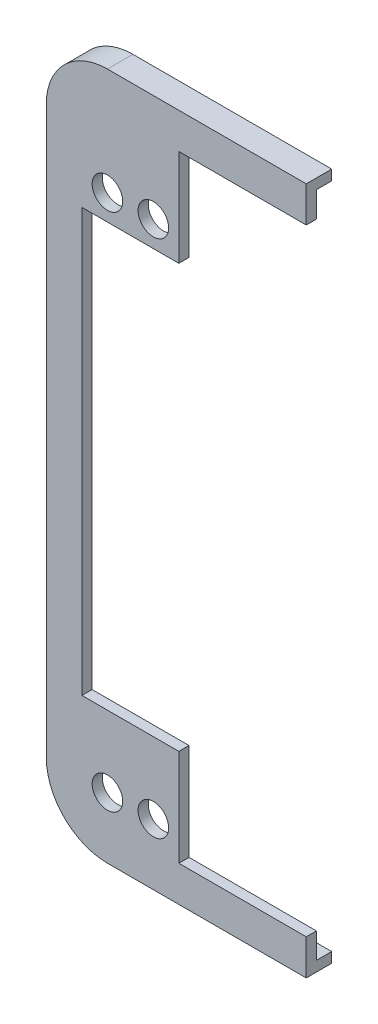
SolidWorks part; units mm, degrees
ref_plane "Front Plane" through (0, 0, 0) normal (0, 0, 1) x (1, 0, 0)
ref_plane "Top Plane" through (0, 0, 0) normal (0, 1, 0) x (1, 0, 0)
ref_plane "Right Plane" through (0, 0, 0) normal (1, 0, 0) x (0, 0, -1)
sketch "Sketch1" plane through (0, 0, 0) normal (0, 0, 1) x (1, 0, 0)
  line L0 (157.8919, 26.2701) -> (191.7747, 29.0915)
  line L1 (157.8919, 26.2701) -> (191.7747, 26.2701)
  line L2 (157.8919, 26.2701) -> (157.8919, 29.0915)
  line L3 (157.8919, 29.0915) -> (191.7747, 29.0915)
  line L4 (191.7747, 26.2701) -> (191.7747, 29.0915)
  line L5 (123.8919, 26.2701) -> (90.0092, 26.2701)
  line L6 (123.8919, 26.2701) -> (123.8919, 29.0915)
  line L7 (123.8919, 29.0915) -> (90.0092, 29.0915)
  line L8 (90.0092, 26.2701) -> (90.0092, 29.0915)
  line L9 (90.0092, 29.0915) -> (123.8919, 26.2701)
  line L10 (168.0919, 58.3601) -> (194.8735, 70.7292)
  line L11 (168.0919, 58.3601) -> (194.8735, 58.3601)
  line L12 (168.0919, 58.3601) -> (168.0919, 70.7292)
  line L13 (168.0919, 70.7292) -> (194.8735, 70.7292)
  line L14 (194.8735, 58.3601) -> (194.8735, 70.7292)
  line L15 (194.8735, 70.7292) -> (224.3587, 70.7292)
  line L16 (194.8735, 70.7292) -> (194.8735, 69.7923)
  line L17 (194.8735, 69.7923) -> (224.3587, 69.7923)
  line L18 (224.3587, 70.7292) -> (224.3587, 69.7923)
  line L19 (224.3587, 69.7923) -> (253.5106, 69.7923)
  line L20 (224.3587, 69.7923) -> (224.3587, 65.2742)
  line L21 (224.3587, 65.2742) -> (253.5106, 65.2742)
  line L22 (253.5106, 69.7923) -> (253.5106, 65.2742)
  line L23 (224.3587, 69.7923) -> (194.8735, 70.7292)
  line L24 (253.5106, 65.2742) -> (224.3587, 69.7923)
  line L25 (170.7502, 87.7401) -> (168.0919, 58.3601)
  line L26 (168.0919, 58.3601) -> (170.7502, 58.3601)
  line L27 (168.0919, 58.3601) -> (168.0919, 87.7401)
  line L28 (168.0919, 87.7401) -> (170.7502, 87.7401)
  line L29 (170.7502, 58.3601) -> (170.7502, 87.7401)
  line L30 (52.9966, 89.4705) -> (24.4119, 82.1791)
  line L31 (24.4119, 82.1791) -> (52.9966, 82.1791)
  line L32 (24.4119, 82.1791) -> (24.4119, 89.4705)
  line L33 (24.4119, 89.4705) -> (52.9966, 89.4705)
  line L34 (52.9966, 82.1791) -> (52.9966, 89.4705)
  line L35 (82.4966, 89.4705) -> (109.0019, 89.4705)
  line L36 (82.4966, 89.4705) -> (82.4966, 76.5201)
  line L37 (82.4966, 76.5201) -> (109.0019, 76.5201)
  line L38 (109.0019, 89.4705) -> (109.0019, 76.5201)
  line L39 (92.4554, 117.2387) -> (82.4966, 117.2387)
  line L40 (92.4554, 117.2387) -> (92.4554, 89.4705)
  line L41 (92.4554, 89.4705) -> (82.4966, 89.4705)
  line L42 (82.4966, 117.2387) -> (82.4966, 89.4705)
  line L43 (92.4554, 117.2387) -> (82.4966, 89.4705)
  line L44 (109.0019, 76.5201) -> (82.4966, 89.4705)
  circle A0 centre (123.8919, 26.2701) radius 14.25
  circle A1 centre (157.8919, 26.2701) radius 14.25
  circle A2 centre (90.0092, 29.0915) radius 14.25
  circle A3 centre (191.7747, 29.0915) radius 14.25
  circle A4 centre (82.4966, 89.4705) radius 11.25
  circle A5 centre (92.4554, 117.2387) radius 11.25
  circle A6 centre (52.9966, 89.4705) radius 11.25
  circle A7 centre (109.0019, 76.5201) radius 11.25
  circle A8 centre (24.4119, 82.1791) radius 11.25
  circle A9 centre (170.7502, 87.7401) radius 11.25
  circle A10 centre (168.0919, 58.3601) radius 11.25
  circle A11 centre (197.5318, 100.1092) radius 11.25
  circle A12 centre (194.8735, 70.7292) radius 11.25
  circle A13 centre (227.0169, 99.1723) radius 11.25
  circle A14 centre (224.3587, 69.7923) radius 11.25
  circle A15 centre (256.1689, 94.6541) radius 11.25
  circle A16 centre (253.5106, 65.2742) radius 11.25
  circle A17 centre (24.4119, 82.1791) radius 12
  circle A18 centre (52.9966, 89.4705) radius 12
  circle A19 centre (92.4554, 117.2387) radius 12
  circle A20 centre (82.4966, 89.4705) radius 12
  circle A21 centre (109.0019, 76.5201) radius 12
  circle A22 centre (168.0919, 58.3601) radius 12
  circle A23 centre (194.8735, 70.7292) radius 12
  circle A24 centre (224.3587, 69.7923) radius 12
  circle A25 centre (253.5106, 65.2742) radius 12
  circle A26 centre (256.1689, 94.6541) radius 12
  circle A27 centre (227.0169, 99.1723) radius 12
  circle A28 centre (197.5318, 100.1092) radius 12
  circle A29 centre (170.7502, 87.7401) radius 12
  circle A30 centre (191.7747, 29.0915) radius 15
  circle A31 centre (157.8919, 26.2701) radius 15
  circle A32 centre (123.8919, 26.2701) radius 15
  circle A33 centre (90.0092, 29.0915) radius 15
  circle A34 centre (173.429, 117.1182) radius 11.25
  circle A35 centre (173.429, 117.1182) radius 12
  dimension "D1" = 28.5
  dimension "D2" = 22.5
  dimension "D3" = 0.75
  dimension "D4" = 0.75
  dimension "D34" = 34
  dimension "D5" = 29.5
  dimension "D6" = 29.5
  dimension "D7" = 29.5
  dimension "D8" = 29.5
  dimension "D9" = 29.5
  dimension "D10" = 29.5
  dimension "D11" = 29.5
  dimension "D12" = 29.5
  dimension "D13" = 29.5
  dimension "D14" = 29.5
  dimension "D15" = 29.5
  dimension "D16" = 29.5
  dimension "D17" = 29.5
  dimension "D18" = 29.5
  dimension "D19" = 34
  dimension "D20" = 34
  dimension "D21" = 32.09
  dimension "D22" = 10.2
  dimension "D23" = 4.76
  dimension "D24" = 4.76
  dimension "D25" = 24.79
  dimension "D26" = 1.82
  dimension "D27" = 8.81
  dimension "D28" = 84.83
  dimension "D29" = 75.69
  dimension "D30" = 70.27
  dimension "D31" = 26.04
  dimension "D32" = 14.89
  dimension "D33" = 50.25
  dimension "D35" = 29.5
  dimension "D36" = 29.5
sketch "Sketch4" plane through (-30.2083, 20.075, 0) normal (0, 0, 1) x (0.9781, -0.2079, 0)
  line L0 (86.1706, 94.1917) -> (105.2206, 75.1417)
  line L1 (67.1206, 94.1917) -> (86.1706, 94.1917)
  line L2 (67.1206, 94.1917) -> (67.1206, 75.1417)
  line L3 (67.1206, 75.1417) -> (86.1706, 75.1417)
  line L4 (86.1706, 94.1917) -> (86.1706, 75.1417)
  line L5 (86.1706, 94.1917) -> (105.2206, 94.1917)
  line L6 (86.1706, 94.1917) -> (86.1706, 75.1417)
  line L7 (86.1706, 75.1417) -> (105.2206, 75.1417)
  line L8 (105.2206, 94.1917) -> (105.2206, 75.1417)
  line L9 (105.2206, 94.1917) -> (124.2706, 94.1917)
  line L10 (105.2206, 94.1917) -> (105.2206, 75.1417)
  line L11 (105.2206, 75.1417) -> (124.2706, 75.1417)
  line L12 (124.2706, 94.1917) -> (124.2706, 75.1417)
  line L13 (86.1706, 94.1917) -> (105.2206, 94.1917)
  line L14 (86.1706, 94.1917) -> (86.1706, 113.2417)
  line L15 (86.1706, 113.2417) -> (105.2206, 113.2417)
  line L16 (105.2206, 94.1917) -> (105.2206, 113.2417)
  line L17 (66.9585, 85.1784) -> (124.4326, 84.1551)
  point P14 (95.6956, 84.6667)
  point P15 (95.6956, 84.6667)
  dimension "D1" = 19.05
sketch "Sketch9" plane through (0, 0, 0) normal (0, 0, 1) x (1, 0, 0)
  line L1 (17.3619, 89.2291) -> (31.4619, 89.2291)
  line L2 (17.3619, 89.2291) -> (17.3619, 75.1291)
  line L3 (17.3619, 75.1291) -> (31.4619, 75.1291)
  line L4 (31.4619, 89.2291) -> (31.4619, 75.1291)
  line L5 (45.9466, 96.5205) -> (60.0466, 96.5205)
  line L6 (45.9466, 96.5205) -> (45.9466, 82.4205)
  line L7 (45.9466, 82.4205) -> (60.0466, 82.4205)
  line L8 (60.0466, 96.5205) -> (60.0466, 82.4205)
  line L9 (75.4466, 96.5205) -> (89.5466, 96.5205)
  line L10 (75.4466, 96.5205) -> (75.4466, 82.4205)
  line L11 (75.4466, 82.4205) -> (89.5466, 82.4205)
  line L12 (89.5466, 96.5205) -> (89.5466, 82.4205)
  line L13 (101.9519, 83.5701) -> (116.0519, 83.5701)
  line L14 (101.9519, 83.5701) -> (101.9519, 69.4701)
  line L15 (101.9519, 69.4701) -> (116.0519, 69.4701)
  line L16 (116.0519, 83.5701) -> (116.0519, 69.4701)
  line L17 (85.4054, 124.2887) -> (99.5054, 124.2887)
  line L18 (85.4054, 124.2887) -> (85.4054, 110.1887)
  line L19 (85.4054, 110.1887) -> (99.5054, 110.1887)
  line L20 (99.5054, 124.2887) -> (99.5054, 110.1887)
  line L21 (82.9592, 36.1415) -> (97.0592, 36.1415)
  line L22 (82.9592, 36.1415) -> (82.9592, 22.0415)
  line L23 (82.9592, 22.0415) -> (97.0592, 22.0415)
  line L24 (97.0592, 36.1415) -> (97.0592, 22.0415)
  line L25 (116.8419, 33.3201) -> (130.9419, 33.3201)
  line L26 (116.8419, 33.3201) -> (116.8419, 19.2201)
  line L27 (116.8419, 19.2201) -> (130.9419, 19.2201)
  line L28 (130.9419, 33.3201) -> (130.9419, 19.2201)
  line L29 (150.8419, 33.3201) -> (164.9419, 33.3201)
  line L30 (150.8419, 33.3201) -> (150.8419, 19.2201)
  line L31 (150.8419, 19.2201) -> (164.9419, 19.2201)
  line L32 (164.9419, 33.3201) -> (164.9419, 19.2201)
  line L33 (184.7247, 36.1415) -> (198.8247, 36.1415)
  line L34 (184.7247, 36.1415) -> (184.7247, 22.0415)
  line L35 (184.7247, 22.0415) -> (198.8247, 22.0415)
  line L36 (198.8247, 36.1415) -> (198.8247, 22.0415)
  line L37 (260.5606, 58.2242) -> (246.4606, 58.2242)
  line L38 (260.5606, 58.2242) -> (260.5606, 72.3242)
  line L39 (260.5606, 72.3242) -> (246.4606, 72.3242)
  line L40 (246.4606, 58.2242) -> (246.4606, 72.3242)
  line L41 (217.3087, 76.8423) -> (231.4087, 76.8423)
  line L42 (217.3087, 76.8423) -> (217.3087, 62.7423)
  line L43 (217.3087, 62.7423) -> (231.4087, 62.7423)
  line L44 (231.4087, 76.8423) -> (231.4087, 62.7423)
  line L45 (187.8235, 77.7792) -> (201.9235, 77.7792)
  line L46 (187.8235, 77.7792) -> (187.8235, 63.6792)
  line L47 (187.8235, 63.6792) -> (201.9235, 63.6792)
  line L48 (201.9235, 77.7792) -> (201.9235, 63.6792)
  line L49 (161.0419, 65.4101) -> (175.1419, 65.4101)
  line L50 (161.0419, 65.4101) -> (161.0419, 51.3101)
  line L51 (161.0419, 51.3101) -> (175.1419, 51.3101)
  line L52 (175.1419, 65.4101) -> (175.1419, 51.3101)
  line L53 (163.7002, 94.7901) -> (177.8002, 94.7901)
  line L54 (163.7002, 94.7901) -> (163.7002, 80.6901)
  line L55 (163.7002, 80.6901) -> (177.8002, 80.6901)
  line L56 (177.8002, 94.7901) -> (177.8002, 80.6901)
  line L57 (190.4818, 107.1592) -> (204.5818, 107.1592)
  line L58 (190.4818, 107.1592) -> (190.4818, 93.0592)
  line L59 (190.4818, 93.0592) -> (204.5818, 93.0592)
  line L60 (204.5818, 107.1592) -> (204.5818, 93.0592)
  line L61 (219.9669, 106.2223) -> (234.0669, 106.2223)
  line L62 (219.9669, 106.2223) -> (219.9669, 92.1223)
  line L63 (219.9669, 92.1223) -> (234.0669, 92.1223)
  line L64 (234.0669, 106.2223) -> (234.0669, 92.1223)
  line L65 (249.1189, 101.7041) -> (263.2189, 101.7041)
  line L66 (249.1189, 101.7041) -> (249.1189, 87.6041)
  line L67 (249.1189, 87.6041) -> (263.2189, 87.6041)
  line L68 (263.2189, 101.7041) -> (263.2189, 87.6041)
  line L69 (166.379, 124.1682) -> (180.479, 124.1682)
  line L70 (166.379, 124.1682) -> (166.379, 110.0682)
  line L71 (166.379, 110.0682) -> (180.479, 110.0682)
  line L72 (180.479, 124.1682) -> (180.479, 110.0682)
  point P72 (24.4119, 89.2291)
  point P74 (52.9966, 96.5205)
  point P76 (82.4966, 96.5205)
  point P78 (92.4554, 124.2887)
  point P80 (109.0019, 83.5701)
  point P82 (90.0092, 36.1415)
  point P84 (123.8919, 33.3201)
  point P86 (157.8919, 33.3201)
  point P88 (191.7747, 36.1415)
  point P90 (168.0919, 65.4101)
  point P92 (170.7502, 94.7901)
  point P94 (173.429, 124.1682)
  point P96 (197.5318, 107.1592)
  point P98 (227.0169, 106.2223)
  point P100 (256.1689, 101.7041)
  point P102 (194.8735, 77.7792)
  point P104 (224.3587, 76.8423)
  point P106 (253.5106, 72.3242)
  point P108 (17.3619, 82.1791)
  point P109 (45.9466, 89.4705)
  point P110 (75.4466, 89.4705)
  point P111 (101.9519, 76.5201)
  point P112 (85.4054, 117.2387)
  point P113 (82.9592, 29.0915)
  point P114 (116.8419, 26.2701)
  point P115 (150.8419, 26.2701)
  point P116 (184.7247, 29.0915)
  point P118 (161.0419, 58.3601)
  point P119 (187.8235, 70.7292)
  point P120 (217.3087, 69.7923)
  point P121 (246.4606, 65.2742)
  point P122 (163.7002, 87.7401)
  point P123 (190.4818, 100.1092)
  point P124 (219.9669, 99.1723)
  point P125 (249.1189, 94.6541)
  point P126 (166.379, 117.1182)
  dimension "D1" = 14.1
sketch "Sketch10" plane through (-22.0981, 19.3454, 0) normal (0, 0, 1) x (0.9781, -0.2079, 0)
  line L1 (61.5108, 90.7441) -> (75.6108, 90.7441)
  line L2 (61.5108, 90.7441) -> (61.5108, 76.6441)
  line L3 (61.5108, 76.6441) -> (75.6108, 76.6441)
  line L4 (75.6108, 90.7441) -> (75.6108, 76.6441)
  line L5 (80.5608, 90.7441) -> (94.6608, 90.7441)
  line L6 (80.5608, 90.7441) -> (80.5608, 76.6441)
  line L7 (80.5608, 76.6441) -> (94.6608, 76.6441)
  line L8 (94.6608, 90.7441) -> (94.6608, 76.6441)
  line L9 (99.6108, 90.7441) -> (113.7108, 90.7441)
  line L10 (99.6108, 90.7441) -> (99.6108, 76.6441)
  line L11 (99.6108, 76.6441) -> (113.7108, 76.6441)
  line L12 (113.7108, 90.7441) -> (113.7108, 76.6441)
  line L13 (80.5608, 109.7941) -> (94.6608, 109.7941)
  line L14 (80.5608, 109.7941) -> (80.5608, 95.6941)
  line L15 (80.5608, 95.6941) -> (94.6608, 95.6941)
  line L16 (94.6608, 109.7941) -> (94.6608, 95.6941)
  line L17 (50.5121, 89.6359) -> (53.4436, 75.8441) construction
  line L18 (59.0358, 93.2191) -> (78.0858, 93.2191) construction
  line L19 (78.0858, 112.2691) -> (97.1358, 112.2691) construction
  line L20 (97.1358, 93.2191) -> (116.1858, 93.2191) construction
  line L21 (78.0858, 93.2191) -> (78.0858, 112.2691) construction
  line L23 (59.0358, 93.2191) -> (59.0358, 74.1691) construction
  point P16 (75.6108, 83.6941)
  point P17 (94.6608, 83.6941)
  point P18 (113.7108, 83.6941)
  point P19 (87.6108, 90.7441)
  point P20 (87.6108, 109.7941)
  point P23 (68.5608, 90.7441)
  point P26 (68.5608, 93.2191)
  point P29 (87.6108, 112.2691)
  point P30 (106.6608, 90.7441)
  point P33 (106.6608, 93.2191)
  point P34 (80.5608, 102.7441)
  point P37 (78.0858, 102.7441)
  point P42 (59.0358, 83.6941)
  point P43 (61.5108, 83.6941)
sketch "Sketch14" plane through (0, 0, 0) normal (0, 0, 1) x (1, 0, 0)
  line L0 (165.1144, 80.6901) -> (163.7002, 82.1043)
  line L1 (163.7002, 93.3758) -> (165.1144, 94.7901)
  line L2 (177.8002, 93.3758) -> (176.386, 94.7901)
  line L3 (179.0648, 110.0682) -> (180.479, 111.4824)
  line L4 (166.379, 111.4824) -> (167.7932, 110.0682)
  line L5 (166.379, 122.754) -> (167.7932, 124.1682)
  line L6 (179.0648, 124.1682) -> (180.479, 122.754)
  line L7 (203.1676, 93.0592) -> (204.5818, 94.4734)
  line L8 (17.3619, 89.2291) -> (17.3619, 75.1291) construction
  line L9 (17.3619, 89.2291) -> (31.4619, 89.2291) construction
  line L10 (17.3619, 87.8149) -> (18.7761, 89.2291)
  line L11 (17.3619, 75.1291) -> (31.4619, 75.1291) construction
  line L12 (31.4619, 89.2291) -> (31.4619, 75.1291) construction
  line L13 (45.9466, 96.5205) -> (60.0466, 96.5205) construction
  line L14 (60.0466, 96.5205) -> (60.0466, 82.4205) construction
  line L15 (45.9466, 96.5205) -> (45.9466, 82.4205) construction
  line L16 (45.9466, 82.4205) -> (60.0466, 82.4205) construction
  line L17 (85.4054, 124.2887) -> (85.4054, 110.1887) construction
  line L18 (85.4054, 124.2887) -> (99.5054, 124.2887) construction
  line L19 (99.5054, 124.2887) -> (99.5054, 110.1887) construction
  line L20 (85.4054, 110.1887) -> (99.5054, 110.1887) construction
  line L21 (101.9519, 83.5701) -> (101.9519, 69.4701) construction
  line L22 (101.9519, 83.5701) -> (116.0519, 83.5701) construction
  line L23 (116.0519, 83.5701) -> (116.0519, 69.4701) construction
  line L24 (101.9519, 69.4701) -> (116.0519, 69.4701) construction
  line L25 (91.2712, 73.6044) -> (105.0631, 70.6729) construction
  line L26 (107.9947, 84.4647) -> (105.0631, 70.6729) construction
  line L27 (94.2028, 87.3963) -> (107.9947, 84.4647) construction
  line L28 (94.2028, 87.3963) -> (91.2712, 73.6044) construction
  line L29 (72.6375, 77.5651) -> (86.4294, 74.6336) construction
  line L30 (89.361, 88.4255) -> (86.4294, 74.6336) construction
  line L31 (75.5691, 91.357) -> (89.361, 88.4255) construction
  line L32 (75.5691, 91.357) -> (72.6375, 77.5651) construction
  line L33 (56.9354, 95.3177) -> (54.0038, 81.5259) construction
  line L34 (56.9354, 95.3177) -> (70.7273, 92.3862) construction
  line L35 (70.7273, 92.3862) -> (67.7957, 78.5943) construction
  line L36 (54.0038, 81.5259) -> (67.7957, 78.5943) construction
  line L37 (76.5983, 96.1988) -> (90.3901, 93.2673) construction
  line L38 (93.3217, 107.0592) -> (90.3901, 93.2673) construction
  line L39 (79.5298, 109.9907) -> (76.5983, 96.1988) construction
  line L40 (79.5298, 109.9907) -> (93.3217, 107.0592) construction
  line L41 (82.9592, 36.1415) -> (82.9592, 22.0415) construction
  line L42 (82.9592, 36.1415) -> (97.0592, 36.1415) construction
  line L43 (82.9592, 22.0415) -> (97.0592, 22.0415) construction
  line L44 (97.0592, 36.1415) -> (97.0592, 22.0415) construction
  line L45 (116.8419, 33.3201) -> (116.8419, 19.2201) construction
  line L46 (116.8419, 33.3201) -> (130.9419, 33.3201) construction
  line L47 (116.8419, 19.2201) -> (130.9419, 19.2201) construction
  line L48 (130.9419, 33.3201) -> (130.9419, 19.2201) construction
  line L49 (150.8419, 33.3201) -> (150.8419, 19.2201) construction
  line L50 (150.8419, 33.3201) -> (164.9419, 33.3201) construction
  line L51 (164.9419, 33.3201) -> (164.9419, 19.2201) construction
  line L52 (150.8419, 19.2201) -> (164.9419, 19.2201) construction
  line L53 (184.7247, 36.1415) -> (184.7247, 22.0415) construction
  line L54 (184.7247, 22.0415) -> (198.8247, 22.0415) construction
  line L55 (198.8247, 36.1415) -> (198.8247, 22.0415) construction
  line L56 (184.7247, 36.1415) -> (198.8247, 36.1415) construction
  line L57 (161.0419, 65.4101) -> (175.1419, 65.4101) construction
  line L58 (175.1419, 65.4101) -> (175.1419, 51.3101) construction
  line L59 (161.0419, 51.3101) -> (175.1419, 51.3101) construction
  line L60 (161.0419, 65.4101) -> (161.0419, 51.3101) construction
  line L61 (187.8235, 77.7792) -> (187.8235, 63.6792) construction
  line L62 (187.8235, 77.7792) -> (201.9235, 77.7792) construction
  line L63 (187.8235, 63.6792) -> (201.9235, 63.6792) construction
  line L64 (201.9235, 77.7792) -> (201.9235, 63.6792) construction
  line L65 (217.3087, 76.8423) -> (217.3087, 62.7423) construction
  line L66 (217.3087, 76.8423) -> (231.4087, 76.8423) construction
  line L67 (231.4087, 76.8423) -> (231.4087, 62.7423) construction
  line L68 (217.3087, 62.7423) -> (231.4087, 62.7423) construction
  line L69 (260.5606, 58.2242) -> (246.4606, 58.2242) construction
  line L70 (260.5606, 58.2242) -> (260.5606, 72.3242) construction
  line L71 (246.4606, 58.2242) -> (246.4606, 72.3242) construction
  line L72 (260.5606, 72.3242) -> (246.4606, 72.3242) construction
  line L73 (249.1189, 101.7041) -> (263.2189, 101.7041) construction
  line L74 (263.2189, 101.7041) -> (263.2189, 87.6041) construction
  line L75 (249.1189, 87.6041) -> (263.2189, 87.6041) construction
  line L76 (249.1189, 101.7041) -> (249.1189, 87.6041) construction
  line L77 (219.9669, 106.2223) -> (219.9669, 92.1223) construction
  line L78 (219.9669, 106.2223) -> (234.0669, 106.2223) construction
  line L79 (234.0669, 106.2223) -> (234.0669, 92.1223) construction
  line L80 (219.9669, 92.1223) -> (234.0669, 92.1223) construction
  line L81 (190.4818, 107.1592) -> (204.5818, 107.1592) construction
  line L82 (204.5818, 107.1592) -> (204.5818, 93.0592) construction
  line L83 (190.4818, 93.0592) -> (204.5818, 93.0592) construction
  line L84 (190.4818, 107.1592) -> (190.4818, 93.0592) construction
  line L85 (163.7002, 94.7901) -> (177.8002, 94.7901) construction
  line L86 (177.8002, 94.7901) -> (177.8002, 80.6901) construction
  line L87 (163.7002, 80.6901) -> (177.8002, 80.6901) construction
  line L88 (163.7002, 94.7901) -> (163.7002, 80.6901) construction
  line L89 (180.479, 124.1682) -> (180.479, 110.0682) construction
  line L90 (166.379, 110.0682) -> (180.479, 110.0682) construction
  line L91 (166.379, 124.1682) -> (166.379, 110.0682) construction
  line L92 (166.379, 124.1682) -> (180.479, 124.1682) construction
  line L93 (17.3619, 76.5433) -> (18.7761, 75.1291)
  line L94 (30.0477, 75.1291) -> (31.4619, 76.5433)
  line L95 (31.4619, 87.8149) -> (30.0477, 89.2291)
  line L96 (45.9466, 95.1063) -> (47.3608, 96.5205)
  line L97 (45.9466, 83.8347) -> (47.3608, 82.4205)
  line L98 (54.2979, 82.9092) -> (55.3871, 81.2318)
  line L99 (58.6323, 82.4205) -> (60.0466, 83.8347)
  line L100 (56.6413, 93.9344) -> (58.3187, 95.0237)
  line L101 (58.6323, 96.5205) -> (60.0466, 95.1063)
  line L102 (69.3439, 92.6802) -> (70.4332, 91.0029)
  line L103 (68.0897, 79.9776) -> (66.4124, 78.8883)
  line L104 (75.2751, 89.9737) -> (76.9524, 91.063)
  line L105 (72.9316, 78.9484) -> (74.0208, 77.2711)
  line L106 (85.0461, 74.9276) -> (86.7234, 76.0169)
  line L107 (89.0669, 87.0421) -> (87.9777, 88.7195)
  line L108 (89.0068, 93.5613) -> (90.6842, 94.6506)
  line L109 (76.8923, 97.5822) -> (77.9816, 95.9048)
  line L110 (91.9384, 107.3532) -> (93.0277, 105.6759)
  line L111 (79.2358, 108.6074) -> (80.9131, 109.6967)
  line L112 (85.4054, 111.6029) -> (86.8196, 110.1887)
  line L113 (98.0912, 110.1887) -> (99.5054, 111.6029)
  line L114 (98.0912, 124.2887) -> (99.5054, 122.8745)
  line L115 (85.4054, 122.8745) -> (86.8196, 124.2887)
  line L116 (93.9088, 86.013) -> (95.5861, 87.1023)
  line L117 (91.5653, 74.9877) -> (92.6546, 73.3104)
  line L118 (103.6798, 70.9669) -> (105.3572, 72.0562)
  line L119 (106.6114, 84.7588) -> (107.7006, 83.0814)
  line L120 (101.9519, 82.1559) -> (103.3662, 83.5701)
  line L121 (101.9519, 70.8843) -> (103.3662, 69.4701)
  line L122 (114.6377, 69.4701) -> (116.0519, 70.8843)
  line L123 (116.0519, 82.1559) -> (114.6377, 83.5701)
  line L124 (82.9592, 34.7272) -> (84.3734, 36.1415)
  line L125 (82.9592, 23.4557) -> (84.3734, 22.0415)
  line L126 (95.645, 22.0415) -> (97.0592, 23.4557)
  line L127 (97.0592, 34.7272) -> (95.645, 36.1415)
  line L128 (116.8419, 31.9059) -> (118.2562, 33.3201)
  line L129 (116.8419, 20.6343) -> (118.2562, 19.2201)
  line L130 (129.5277, 19.2201) -> (130.9419, 20.6343)
  line L131 (130.9419, 31.9059) -> (129.5277, 33.3201)
  line L132 (150.8419, 31.9059) -> (152.2562, 33.3201)
  line L133 (150.8419, 20.6343) -> (152.2562, 19.2201)
  line L134 (163.5277, 19.2201) -> (164.9419, 20.6343)
  line L135 (164.9419, 31.9059) -> (163.5277, 33.3201)
  line L136 (184.7247, 34.7272) -> (186.1389, 36.1415)
  line L137 (184.7247, 23.4557) -> (186.1389, 22.0415)
  line L138 (197.4105, 22.0415) -> (198.8247, 23.4557)
  line L139 (198.8247, 34.7272) -> (197.4105, 36.1415)
  line L140 (173.7277, 51.3101) -> (175.1419, 52.7243)
  line L141 (161.0419, 52.7243) -> (162.4562, 51.3101)
  line L142 (161.0419, 63.9959) -> (162.4562, 65.4101)
  line L143 (173.7277, 65.4101) -> (175.1419, 63.9959)
  line L144 (187.8235, 65.0934) -> (189.2378, 63.6792)
  line L145 (200.5093, 63.6792) -> (201.9235, 65.0934)
  line L146 (200.5093, 77.7792) -> (201.9235, 76.365)
  line L147 (187.8235, 76.365) -> (189.2378, 77.7792)
  line L148 (176.386, 80.6901) -> (177.8002, 82.1043)
  line L149 (204.5818, 105.745) -> (203.1676, 107.1592)
  line L150 (191.896, 107.1592) -> (190.4818, 105.745)
  line L151 (190.4818, 94.4734) -> (191.896, 93.0592)
  line L152 (219.9669, 104.8081) -> (221.3812, 106.2223)
  line L153 (232.6527, 106.2223) -> (234.0669, 104.8081)
  line L154 (234.0669, 93.5365) -> (232.6527, 92.1223)
  line L155 (219.9669, 93.5365) -> (221.3812, 92.1223)
  line L156 (229.9944, 76.8423) -> (231.4087, 75.4281)
  line L157 (217.3087, 75.4281) -> (218.7229, 76.8423)
  line L158 (217.3087, 64.1565) -> (218.7229, 62.7423)
  line L159 (229.9944, 62.7423) -> (231.4087, 64.1565)
  line L160 (259.1464, 72.3242) -> (260.5606, 70.9099)
  line L161 (246.4606, 70.9099) -> (247.8748, 72.3242)
  line L162 (259.1464, 58.2242) -> (260.5606, 59.6384)
  line L163 (247.8748, 58.2242) -> (246.4606, 59.6384)
  line L164 (261.8047, 87.6041) -> (263.2189, 89.0183)
  line L165 (249.1189, 89.0183) -> (250.5331, 87.6041)
  line L166 (249.1189, 100.2899) -> (250.5331, 101.7041)
  line L167 (261.8047, 101.7041) -> (263.2189, 100.2899)
  line L168 (75.4466, 96.5205) -> (75.4466, 82.4205) construction
  line L169 (75.4466, 96.5205) -> (89.5466, 96.5205) construction
  line L170 (89.5466, 96.5205) -> (89.5466, 82.4205) construction
  line L171 (75.4466, 82.4205) -> (89.5466, 82.4205) construction
  line L172 (76.8608, 96.5205) -> (75.4466, 95.1063)
  line L173 (88.1323, 96.5205) -> (89.5466, 95.1063)
  line L174 (89.5466, 83.8347) -> (88.1323, 82.4205)
  line L175 (75.4466, 83.8347) -> (76.8608, 82.4205)
  arc A0 (17.3619, 87.8149) -> (18.7761, 89.2291) centre (18.069, 88.522) cw
  arc A1 (18.7761, 75.1291) -> (17.3619, 76.5433) centre (18.069, 75.8362) cw
  arc A2 (31.4619, 76.5433) -> (30.0477, 75.1291) centre (30.7548, 75.8362) cw
  arc A3 (30.0477, 89.2291) -> (31.4619, 87.8149) centre (30.7548, 88.522) cw
  arc A4 (58.6323, 96.5205) -> (60.0466, 95.1063) centre (59.3394, 95.8134) cw
  arc A5 (45.9466, 95.1063) -> (47.3608, 96.5205) centre (46.6537, 95.8134) cw
  arc A6 (47.3608, 82.4205) -> (45.9466, 83.8347) centre (46.6537, 83.1276) cw
  arc A7 (60.0466, 83.8347) -> (58.6323, 82.4205) centre (59.3394, 83.1276) cw
  arc A8 (85.4054, 122.8745) -> (86.8196, 124.2887) centre (86.1125, 123.5816) cw
  arc A9 (98.0912, 124.2887) -> (99.5054, 122.8745) centre (98.7983, 123.5816) cw
  arc A10 (99.5054, 111.6029) -> (98.0912, 110.1887) centre (98.7983, 110.8958) cw
  arc A11 (85.4054, 111.6029) -> (86.8196, 110.1887) centre (86.1125, 110.8958) ccw
  arc A12 (101.9519, 82.1559) -> (103.3662, 83.5701) centre (102.6591, 82.863) cw
  arc A13 (114.6377, 83.5701) -> (116.0519, 82.1559) centre (115.3448, 82.863) cw
  arc A14 (116.0519, 70.8843) -> (114.6377, 69.4701) centre (115.3448, 70.1772) cw
  arc A15 (101.9519, 70.8843) -> (103.3662, 69.4701) centre (102.6591, 70.1772) ccw
  arc A16 (103.6798, 70.9669) -> (105.3572, 72.0562) centre (104.5185, 71.5115) ccw
  arc A17 (106.6114, 84.7588) -> (107.7006, 83.0814) centre (107.156, 83.9201) cw
  arc A18 (93.9088, 86.013) -> (95.5861, 87.1023) centre (94.7474, 86.5576) cw
  arc A19 (91.5653, 74.9877) -> (92.6546, 73.3104) centre (92.1099, 74.1491) ccw
  arc A20 (85.0461, 74.9276) -> (86.7234, 76.0169) centre (85.8848, 75.4722) ccw
  arc A21 (87.9777, 88.7195) -> (89.0669, 87.0421) centre (88.5223, 87.8808) cw
  arc A22 (75.2751, 89.9737) -> (76.9524, 91.063) centre (76.1137, 90.5183) cw
  arc A23 (72.9316, 78.9484) -> (74.0208, 77.2711) centre (73.4762, 78.1098) ccw
  arc A24 (56.6413, 93.9344) -> (58.3187, 95.0237) centre (57.48, 94.4791) cw
  arc A25 (69.3439, 92.6802) -> (70.4332, 91.0029) centre (69.8886, 91.8415) cw
  arc A26 (68.0897, 79.9776) -> (66.4124, 78.8883) centre (67.2511, 79.433) cw
  arc A27 (54.2979, 82.9092) -> (55.3871, 81.2318) centre (54.8425, 82.0705) ccw
  arc A28 (89.0068, 93.5613) -> (90.6842, 94.6506) centre (89.8455, 94.106) ccw
  arc A29 (76.8923, 97.5822) -> (77.9816, 95.9048) centre (77.4369, 96.7435) ccw
  arc A30 (79.2358, 108.6074) -> (80.9131, 109.6967) centre (80.0744, 109.1521) cw
  arc A31 (91.9384, 107.3532) -> (93.0277, 105.6759) centre (92.483, 106.5145) cw
  arc A32 (82.9592, 34.7272) -> (84.3734, 36.1415) centre (83.6663, 35.4344) cw
  arc A33 (82.9592, 23.4557) -> (84.3734, 22.0415) centre (83.6663, 22.7486) ccw
  arc A34 (95.645, 22.0415) -> (97.0592, 23.4557) centre (96.3521, 22.7486) ccw
  arc A35 (95.645, 36.1415) -> (97.0592, 34.7272) centre (96.3521, 35.4344) cw
  arc A36 (116.8419, 31.9059) -> (118.2562, 33.3201) centre (117.5491, 32.613) cw
  arc A37 (116.8419, 20.6343) -> (118.2562, 19.2201) centre (117.5491, 19.9272) ccw
  arc A38 (129.5277, 19.2201) -> (130.9419, 20.6343) centre (130.2348, 19.9272) ccw
  arc A39 (129.5277, 33.3201) -> (130.9419, 31.9059) centre (130.2348, 32.613) cw
  arc A40 (150.8419, 31.9059) -> (152.2562, 33.3201) centre (151.5491, 32.613) cw
  arc A41 (163.5277, 33.3201) -> (164.9419, 31.9059) centre (164.2348, 32.613) cw
  arc A42 (164.9419, 20.6343) -> (163.5277, 19.2201) centre (164.2348, 19.9272) cw
  arc A43 (150.8419, 20.6343) -> (152.2562, 19.2201) centre (151.5491, 19.9272) ccw
  arc A44 (184.7247, 23.4557) -> (186.1389, 22.0415) centre (185.4318, 22.7486) ccw
  arc A45 (197.4105, 22.0415) -> (198.8247, 23.4557) centre (198.1176, 22.7486) ccw
  arc A46 (197.4105, 36.1415) -> (198.8247, 34.7272) centre (198.1176, 35.4344) cw
  arc A47 (184.7247, 34.7272) -> (186.1389, 36.1415) centre (185.4318, 35.4344) cw
  arc A48 (173.7277, 65.4101) -> (175.1419, 63.9959) centre (174.4348, 64.703) cw
  arc A49 (175.1419, 52.7243) -> (173.7277, 51.3101) centre (174.4348, 52.0172) cw
  arc A50 (161.0419, 52.7243) -> (162.4562, 51.3101) centre (161.7491, 52.0172) ccw
  arc A51 (161.0419, 63.9959) -> (162.4562, 65.4101) centre (161.7491, 64.703) cw
  arc A52 (187.8235, 76.365) -> (189.2378, 77.7792) centre (188.5306, 77.0721) cw
  arc A53 (187.8235, 65.0934) -> (189.2378, 63.6792) centre (188.5306, 64.3863) ccw
  arc A54 (200.5093, 63.6792) -> (201.9235, 65.0934) centre (201.2164, 64.3863) ccw
  arc A55 (200.5093, 77.7792) -> (201.9235, 76.365) centre (201.2164, 77.0721) cw
  arc A56 (217.3087, 75.4281) -> (218.7229, 76.8423) centre (218.0158, 76.1352) cw
  arc A57 (229.9944, 76.8423) -> (231.4087, 75.4281) centre (230.7016, 76.1352) cw
  arc A58 (231.4087, 64.1565) -> (229.9944, 62.7423) centre (230.7016, 63.4494) cw
  arc A59 (217.3087, 64.1565) -> (218.7229, 62.7423) centre (218.0158, 63.4494) ccw
  arc A60 (259.1464, 58.2242) -> (260.5606, 59.6384) centre (259.8535, 58.9313) ccw
  arc A61 (246.4606, 59.6384) -> (247.8748, 58.2242) centre (247.1677, 58.9313) ccw
  arc A62 (246.4606, 70.9099) -> (247.8748, 72.3242) centre (247.1677, 71.617) cw
  arc A63 (259.1464, 72.3242) -> (260.5606, 70.9099) centre (259.8535, 71.617) cw
  arc A64 (261.8047, 101.7041) -> (263.2189, 100.2899) centre (262.5118, 100.997) cw
  arc A65 (263.2189, 89.0183) -> (261.8047, 87.6041) centre (262.5118, 88.3112) cw
  arc A66 (250.5331, 87.6041) -> (249.1189, 89.0183) centre (249.826, 88.3112) cw
  arc A67 (249.1189, 100.2899) -> (250.5331, 101.7041) centre (249.826, 100.997) cw
  arc A68 (219.9669, 104.8081) -> (221.3812, 106.2223) centre (220.674, 105.5152) cw
  arc A69 (232.6527, 106.2223) -> (234.0669, 104.8081) centre (233.3598, 105.5152) cw
  arc A70 (234.0669, 93.5365) -> (232.6527, 92.1223) centre (233.3598, 92.8294) cw
  arc A71 (221.3812, 92.1223) -> (219.9669, 93.5365) centre (220.674, 92.8294) cw
  arc A72 (203.1676, 107.1592) -> (204.5818, 105.745) centre (203.8747, 106.4521) cw
  arc A73 (204.5818, 94.4734) -> (203.1676, 93.0592) centre (203.8747, 93.7663) cw
  arc A74 (191.896, 93.0592) -> (190.4818, 94.4734) centre (191.1889, 93.7663) cw
  arc A75 (190.4818, 105.745) -> (191.896, 107.1592) centre (191.1889, 106.4521) cw
  arc A76 (176.386, 94.7901) -> (177.8002, 93.3758) centre (177.0931, 94.0829) cw
  arc A77 (177.8002, 82.1043) -> (176.386, 80.6901) centre (177.0931, 81.3972) cw
  arc A78 (165.1144, 80.6901) -> (163.7002, 82.1043) centre (164.4073, 81.3972) cw
  arc A79 (163.7002, 93.3758) -> (165.1144, 94.7901) centre (164.4073, 94.0829) cw
  arc A80 (180.479, 111.4824) -> (179.0648, 110.0682) centre (179.7719, 110.7753) cw
  arc A81 (167.7932, 110.0682) -> (166.379, 111.4824) centre (167.0861, 110.7753) cw
  arc A82 (179.0648, 124.1682) -> (180.479, 122.754) centre (179.7719, 123.4611) cw
  arc A83 (166.379, 122.754) -> (167.7932, 124.1682) centre (167.0861, 123.4611) cw
  arc A84 (75.4466, 95.1063) -> (76.8608, 96.5205) centre (76.1537, 95.8134) cw
  arc A85 (88.1323, 96.5205) -> (89.5466, 95.1063) centre (88.8394, 95.8134) cw
  arc A86 (89.5466, 83.8347) -> (88.1323, 82.4205) centre (88.8394, 83.1276) cw
  arc A87 (76.8608, 82.4205) -> (75.4466, 83.8347) centre (76.1537, 83.1276) cw
  dimension "D1" = 45
  dimension "D2" = 1
  dimension "D71" = 45
  dimension "D3" = 45
  dimension "D4" = 45
  dimension "D5" = 45
  dimension "D6" = 45
  dimension "D7" = 45
  dimension "D8" = 45
  dimension "D9" = 45
  dimension "D10" = 45
  dimension "D11" = 45
  dimension "D12" = 45
  dimension "D13" = 45
  dimension "D14" = 45
  dimension "D15" = 45
  dimension "D16" = 45
  dimension "D17" = 45
  dimension "D18" = 45
  dimension "D19" = 45
  dimension "D20" = 45
  dimension "D21" = 45
  dimension "D22" = 45
  dimension "D23" = 45
  dimension "D24" = 45
  dimension "D25" = 45
  dimension "D26" = 45
  dimension "D27" = 45
  dimension "D28" = 45
  dimension "D29" = 45
  dimension "D30" = 45
  dimension "D31" = 45
  dimension "D32" = 45
  dimension "D33" = 45
  dimension "D34" = 45
  dimension "D35" = 45
  dimension "D36" = 45
  dimension "D37" = 45
  dimension "D38" = 45
  dimension "D39" = 45
  dimension "D40" = 45
  dimension "D41" = 45
  dimension "D42" = 45
  dimension "D43" = 45
  dimension "D44" = 45
  dimension "D45" = 45
  dimension "D46" = 45
  dimension "D47" = 45
  dimension "D48" = 45
  dimension "D49" = 45
  dimension "D50" = 45
  dimension "D51" = 45
  dimension "D52" = 45
  dimension "D53" = 45
  dimension "D54" = 45
  dimension "D55" = 45
  dimension "D56" = 45
  dimension "D57" = 45
  dimension "D58" = 45
  dimension "D59" = 45
  dimension "D60" = 45
  dimension "D61" = 45
  dimension "D62" = 45
  dimension "D63" = 45
  dimension "D64" = 45
  dimension "D65" = 45
  dimension "D66" = 45
  dimension "D67" = 45
  dimension "D68" = 45
  dimension "D69" = 45
  dimension "D70" = 45
  dimension "D72" = 45
  dimension "D73" = 45
  dimension "D74" = 45
  dimension "D75" = 45
  dimension "D76" = 45
  dimension "D77" = 45
  dimension "D78" = 45
  dimension "D79" = 45
  dimension "D80" = 45
  dimension "D81" = 45
  dimension "D82" = 45
  dimension "D83" = 45
  dimension "D84" = 45
  dimension "D85" = 45
  dimension "D86" = 45
  dimension "D87" = 45
  dimension "D88" = 45
  dimension "D89" = 45
sketch "Sketch16" plane through (0, 0, 0) normal (0, 0, 1) x (1, 0, 0)
  line L0 (81.0092, 30.6915) -> (99.0092, 30.6915)
  line L5 (17.3619, 89.2291) -> (17.3619, 75.1291) construction
  line L6 (81.0092, 30.6915) -> (81.0092, 27.4915)
  line L7 (17.3619, 75.1291) -> (31.4619, 75.1291) construction
  line L8 (15.4119, 83.7791) -> (33.4119, 83.7791)
  line L9 (15.4119, 83.7791) -> (15.4119, 80.5791)
  line L10 (15.4119, 80.5791) -> (33.4119, 80.5791)
  line L11 (33.4119, 83.7791) -> (33.4119, 80.5791)
  line L12 (81.0092, 27.4915) -> (99.0092, 27.4915)
  line L13 (99.0092, 30.6915) -> (99.0092, 27.4915)
  line L14 (114.8919, 27.8701) -> (132.8919, 27.8701)
  line L15 (114.8919, 27.8701) -> (114.8919, 24.6701)
  line L16 (114.8919, 24.6701) -> (132.8919, 24.6701)
  line L17 (132.8919, 27.8701) -> (132.8919, 24.6701)
  line L18 (148.8919, 27.8701) -> (166.8919, 27.8701)
  line L19 (148.8919, 27.8701) -> (148.8919, 24.6701)
  line L20 (148.8919, 24.6701) -> (166.8919, 24.6701)
  line L21 (166.8919, 27.8701) -> (166.8919, 24.6701)
  line L22 (182.7747, 30.6915) -> (200.7747, 30.6915)
  line L23 (182.7747, 30.6915) -> (182.7747, 27.4915)
  line L24 (182.7747, 27.4915) -> (200.7747, 27.4915)
  line L25 (200.7747, 30.6915) -> (200.7747, 27.4915)
  line L26 (43.9966, 91.0705) -> (61.9966, 91.0705)
  line L27 (43.9966, 91.0705) -> (43.9966, 87.8705)
  line L28 (43.9966, 87.8705) -> (61.9966, 87.8705)
  line L29 (61.9966, 91.0705) -> (61.9966, 87.8705)
  line L30 (73.4966, 91.0705) -> (91.4966, 91.0705)
  line L31 (73.4966, 91.0705) -> (73.4966, 87.8705)
  line L32 (73.4966, 87.8705) -> (91.4966, 87.8705)
  line L33 (91.4966, 91.0705) -> (91.4966, 87.8705)
  line L34 (100.0019, 78.1201) -> (118.0019, 78.1201)
  line L35 (100.0019, 78.1201) -> (100.0019, 74.9201)
  line L36 (100.0019, 74.9201) -> (118.0019, 74.9201)
  line L37 (118.0019, 78.1201) -> (118.0019, 74.9201)
  line L38 (83.4554, 118.8387) -> (101.4554, 118.8387)
  line L39 (83.4554, 118.8387) -> (83.4554, 115.6387)
  line L40 (83.4554, 115.6387) -> (101.4554, 115.6387)
  line L41 (101.4554, 118.8387) -> (101.4554, 115.6387)
  line L42 (164.429, 118.7182) -> (182.429, 118.7182)
  line L43 (164.429, 118.7182) -> (164.429, 115.5182)
  line L44 (164.429, 115.5182) -> (182.429, 115.5182)
  line L45 (182.429, 118.7182) -> (182.429, 115.5182)
  line L46 (161.7502, 89.3401) -> (179.7502, 89.3401)
  line L47 (161.7502, 89.3401) -> (161.7502, 86.1401)
  line L48 (161.7502, 86.1401) -> (179.7502, 86.1401)
  line L49 (179.7502, 89.3401) -> (179.7502, 86.1401)
  line L50 (188.5318, 101.7092) -> (206.5318, 101.7092)
  line L51 (188.5318, 101.7092) -> (188.5318, 98.5092)
  line L52 (188.5318, 98.5092) -> (206.5318, 98.5092)
  line L53 (206.5318, 101.7092) -> (206.5318, 98.5092)
  line L54 (159.0919, 59.9601) -> (177.0919, 59.9601)
  line L55 (159.0919, 59.9601) -> (159.0919, 56.7601)
  line L56 (159.0919, 56.7601) -> (177.0919, 56.7601)
  line L57 (177.0919, 59.9601) -> (177.0919, 56.7601)
  line L58 (185.8735, 72.3292) -> (203.8735, 72.3292)
  line L59 (185.8735, 72.3292) -> (185.8735, 69.1292)
  line L60 (185.8735, 69.1292) -> (203.8735, 69.1292)
  line L61 (203.8735, 72.3292) -> (203.8735, 69.1292)
  line L62 (218.0169, 100.7723) -> (236.0169, 100.7723)
  line L63 (218.0169, 100.7723) -> (218.0169, 97.5723)
  line L64 (218.0169, 97.5723) -> (236.0169, 97.5723)
  line L65 (236.0169, 100.7723) -> (236.0169, 97.5723)
  line L66 (215.3587, 71.3923) -> (233.3587, 71.3923)
  line L67 (215.3587, 71.3923) -> (215.3587, 68.1923)
  line L68 (215.3587, 68.1923) -> (233.3587, 68.1923)
  line L69 (233.3587, 71.3923) -> (233.3587, 68.1923)
  line L70 (247.1689, 96.2541) -> (265.1689, 96.2541)
  line L71 (247.1689, 96.2541) -> (247.1689, 93.0541)
  line L72 (247.1689, 93.0541) -> (265.1689, 93.0541)
  line L73 (265.1689, 96.2541) -> (265.1689, 93.0541)
  line L74 (244.5106, 66.8742) -> (262.5106, 66.8742)
  line L75 (244.5106, 66.8742) -> (244.5106, 63.6742)
  line L76 (244.5106, 63.6742) -> (262.5106, 63.6742)
  line L77 (262.5106, 66.8742) -> (262.5106, 63.6742)
  circle A0 centre (15.4119, 82.1791) radius 1.6
  circle A1 centre (33.4119, 82.1791) radius 1.6
  circle A2 centre (81.0092, 29.0915) radius 1.6
  circle A3 centre (99.0092, 29.0915) radius 1.6
  circle A4 centre (114.8919, 26.2701) radius 1.6
  circle A5 centre (132.8919, 26.2701) radius 1.6
  circle A6 centre (148.8919, 26.2701) radius 1.6
  circle A7 centre (166.8919, 26.2701) radius 1.6
  circle A8 centre (182.7747, 29.0915) radius 1.6
  circle A9 centre (200.7747, 29.0915) radius 1.6
  circle A10 centre (43.9966, 89.4705) radius 1.6
  circle A11 centre (61.9966, 89.4705) radius 1.6
  circle A12 centre (73.4966, 89.4705) radius 1.6
  circle A13 centre (91.4966, 89.4705) radius 1.6
  circle A14 centre (100.0019, 76.5201) radius 1.6
  circle A15 centre (118.0019, 76.5201) radius 1.6
  circle A16 centre (83.4554, 117.2387) radius 1.6
  circle A17 centre (101.4554, 117.2387) radius 1.6
  circle A18 centre (164.429, 117.1182) radius 1.6
  circle A19 centre (182.429, 117.1182) radius 1.6
  circle A20 centre (161.7502, 87.7401) radius 1.6
  circle A21 centre (179.7502, 87.7401) radius 1.6
  circle A22 centre (188.5318, 100.1092) radius 1.6
  circle A23 centre (206.5318, 100.1092) radius 1.6
  circle A24 centre (159.0919, 58.3601) radius 1.6
  circle A25 centre (177.0919, 58.3601) radius 1.6
  circle A26 centre (185.8735, 70.7292) radius 1.6
  circle A27 centre (203.8735, 70.7292) radius 1.6
  circle A28 centre (218.0169, 99.1723) radius 1.6
  circle A29 centre (236.0169, 99.1723) radius 1.6
  circle A30 centre (215.3587, 69.7923) radius 1.6
  circle A31 centre (233.3587, 69.7923) radius 1.6
  circle A32 centre (247.1689, 94.6541) radius 1.6
  circle A33 centre (265.1689, 94.6541) radius 1.6
  circle A34 centre (244.5106, 65.2742) radius 1.6
  circle A35 centre (262.5106, 65.2742) radius 1.6
  point P2 (24.4119, 75.1291)
  point P6 (17.3619, 82.1791)
  point P14 (24.4119, 80.5791)
  point P53 (90.0092, 30.6915)
  point P57 (123.8919, 27.8701)
  point P60 (157.8919, 27.8701)
  point P63 (191.7747, 30.6915)
  point P73 (52.9966, 91.0705)
  point P83 (82.4966, 91.0705)
  point P93 (109.0019, 78.1201)
  point P103 (92.4554, 118.8387)
  point P113 (173.429, 118.7182)
  point P123 (170.7502, 89.3401)
  point P133 (197.5318, 101.7092)
  point P143 (168.0919, 59.9601)
  point P153 (194.8735, 72.3292)
  point P163 (227.0169, 100.7723)
  point P173 (224.3587, 71.3923)
  point P183 (256.1689, 96.2541)
  point P193 (253.5106, 66.8742)
  dimension "D1" = 3.2
  dimension "D2" = 18
sketch "Sketch8" plane through (0, 0, 0) normal (0, 0, 1) x (1, 0, 0)
  line L0 (52.2844, 74.6389) -> (82.4966, 89.4705)
  line L1 (86.9403, 110.9459) -> (79.0189, 73.6784)
  line L2 (77.6235, 112.9262) -> (96.2572, 108.9655) construction
  line L3 (69.702, 75.6588) -> (88.3357, 71.6981) construction
  line L4 (53.3861, 72.3947) -> (55.5425, 73.4534)
  line L5 (99.6829, 63.2465) -> (101.1557, 61.3487)
  line L6 (103.1308, 62.8814) -> (82.4966, 89.4705)
  line L13 (93.9017, 130.158) -> (94.0202, 130.4883)
  line L14 (99.5495, 128.1325) -> (99.6679, 128.4628)
  line L16 (99.4417, 62.7418) -> (100.7607, 61.0421)
  line L17 (55.5377, 72.894) -> (53.6064, 71.9459)
  line L19 (82.4966, 89.4705) -> (96.8441, 129.4755)
  circle A1 centre (57.4203, 106.4022) radius 2.5
  circle A2 centre (106.0456, 106.2134) radius 2.5
  circle A3 centre (76.7673, 63.0854) radius 2.5
  circle A4 centre (52.9966, 89.4705) radius 13
  circle A6 centre (92.4554, 117.2387) radius 13
  circle A7 centre (109.0019, 76.5201) radius 13
  circle A8 centre (82.4966, 89.4705) radius 25
  arc A10 (50.3337, 102.1949) -> (81.377, 124.0408) centre (40.5107, 149.1329) ccw
  circle A11 centre (103.1308, 62.8814) radius 2.5
  circle A12 centre (52.2844, 74.6389) radius 2.5
  circle A13 centre (96.8441, 129.4755) radius 2.5
  circle A14 centre (52.2844, 74.6389) radius 3
  circle A15 centre (103.1308, 62.8814) radius 3
  circle A16 centre (96.8441, 129.4755) radius 3
  arc A17 (104.9258, 113.5659) -> (115.3756, 87.8504) centre (126.3001, 107.2707) ccw
  arc A18 (45.7038, 78.7088) -> (110.8301, 63.6492) centre (97.7768, 155.5511) ccw
  circle A19 centre (92.4554, 117.2387) radius 15
  circle A20 centre (109.0019, 76.5201) radius 15
  circle A21 centre (52.9966, 89.4705) radius 15
  circle A22 centre (82.4966, 89.4705) radius 27
  arc A23 (44.5818, 77.0531) -> (111.1113, 61.6691) centre (97.7768, 155.5511) ccw
  arc A24 (49.924, 104.1525) -> (79.6727, 125.0873) centre (40.5107, 149.1329) ccw
  arc A25 (106.8443, 113.0008) -> (116.3562, 89.5935) centre (126.3001, 107.2707) ccw
  circle A26 centre (52.9966, 89.4705) radius 12.5
  circle A27 centre (109.0019, 76.5201) radius 12.5
  circle A28 centre (92.4554, 117.2387) radius 12.5
  circle A29 centre (82.4966, 89.4705) radius 24.5
  arc A30 (104.4462, 113.7071) -> (115.1305, 87.4146) centre (126.3001, 107.2707) ccw
  arc A31 (110.7597, 64.1443) -> (45.9842, 79.1227) centre (97.7768, 155.5511) cw
  arc A32 (50.4361, 101.7055) -> (81.8031, 123.7792) centre (40.5107, 149.1329) ccw
  circle A33 centre (52.9966, 89.4705) radius 15.5
  circle A34 centre (109.0019, 76.5201) radius 15.5
  circle A35 centre (92.4554, 117.2387) radius 15.5
  circle A36 centre (82.4966, 89.4705) radius 27.5
  arc A37 (107.3239, 112.8596) -> (116.6013, 90.0293) centre (126.3001, 107.2707) ccw
  arc A38 (111.1816, 61.1741) -> (44.3013, 76.6392) centre (97.7768, 155.5511) cw
  arc A39 (49.8216, 104.6419) -> (79.2466, 125.349) centre (40.5107, 149.1329) ccw
  circle A40 centre (106.0456, 106.2134) radius 3
  circle A41 centre (76.7673, 63.0854) radius 3
  circle A42 centre (57.4203, 106.4022) radius 3
  dimension "D3" = 26
  dimension "D4" = 5
  dimension "D7" = 6
  dimension "D8" = 50
  dimension "D1" = 2
  dimension "D2" = 2
  dimension "D5" = 0.5
  dimension "D6" = 0.5
  dimension "D9" = 0.5
  dimension "D10" = 0.5
sketch "Sketch2" plane through (0, 0, 0) normal (0, 0, 1) x (1, 0, 0)
  line L0 (30.4119, 134.2387) -> (8.4119, 112.2387)
  line L1 (16.4119, 134.2387) -> (264.1689, 134.2387)
  line L2 (8.4119, 126.2387) -> (8.4119, 15.2864)
  line L3 (16.4119, 7.2864) -> (264.1689, 7.2864)
  line L4 (272.1689, 126.2387) -> (272.1689, 15.2864)
  line L5 (16.4119, 136.2387) -> (264.1689, 136.2387)
  line L6 (6.4119, 126.2387) -> (6.4119, 15.2864)
  line L7 (16.4119, 5.2864) -> (264.1689, 5.2864)
  line L8 (274.1689, 126.2387) -> (274.1689, 15.2864)
  line L9 (250.1689, 134.2387) -> (272.1689, 112.2387)
  line L10 (6.4119, 110.2387) -> (32.4119, 136.2387)
  line L11 (248.1689, 136.2387) -> (274.1689, 110.2387)
  line L12 (6.4119, 107.4103) -> (35.2403, 136.2387)
  line L13 (245.3405, 136.2387) -> (274.1689, 107.4103)
  circle A0 centre (24.4119, 82.1791) radius 12 construction
  circle A2 centre (256.1689, 94.6541) radius 12 construction
  arc A3 (264.1689, 136.2387) -> (274.1689, 126.2387) centre (264.1689, 126.2387) cw
  circle A4 centre (123.8919, 26.2701) radius 15 construction
  arc A5 (264.1689, 5.2864) -> (274.1689, 15.2864) centre (264.1689, 15.2864) ccw
  arc A6 (6.4119, 15.2864) -> (16.4119, 5.2864) centre (16.4119, 15.2864) ccw
  arc A7 (16.4119, 136.2387) -> (6.4119, 126.2387) centre (16.4119, 126.2387) ccw
  arc A8 (264.1689, 134.2387) -> (272.1689, 126.2387) centre (264.1689, 126.2387) cw
  arc A9 (264.1689, 7.2864) -> (272.1689, 15.2864) centre (264.1689, 15.2864) ccw
  arc A10 (8.4119, 15.2864) -> (16.4119, 7.2864) centre (16.4119, 15.2864) ccw
  arc A11 (16.4119, 134.2387) -> (8.4119, 126.2387) centre (16.4119, 126.2387) ccw
  circle A12 centre (92.4554, 117.2387) radius 13 construction
  point P4 (12.4119, 82.1791)
  point P5 (92.4554, 130.2387)
  point P8 (268.1689, 94.6541)
  point P14 (124.5912, 11.2864)
  point P36 (30.4119, 134.2387)
  point P39 (250.1689, 134.2387)
  dimension "D9" = 10
  dimension "D10" = 8
  dimension "D1" = 4
  dimension "D2" = 4
  dimension "D3" = 4
  dimension "D4" = 4
  dimension "D5" = 2
  dimension "D6" = 2
  dimension "D7" = 2
  dimension "D8" = 2
  dimension "D11" = 14
  dimension "D12" = 45
  dimension "D13" = 14
  dimension "D14" = 45
  dimension "D15" = 2
  dimension "D16" = 2
sketch "Sketch6" plane through (0, 0, 0) normal (0, 0, 1) x (1, 0, 0)
  line L0 (44.9119, 130.2387) -> (56.9119, 130.2387)
  line L1 (31.4119, 130.2387) -> (43.4119, 130.2387)
  line L2 (31.4119, 130.2387) -> (31.4119, 118.2387)
  line L3 (31.4119, 118.2387) -> (43.4119, 118.2387)
  line L4 (43.4119, 130.2387) -> (43.4119, 118.2387)
  line L5 (34.1619, 133.2387) -> (40.6619, 133.2387)
  line L6 (34.1619, 133.2387) -> (34.1619, 115.2387)
  line L7 (34.1619, 115.2387) -> (40.6619, 115.2387)
  line L8 (40.6619, 133.2387) -> (40.6619, 115.2387)
  line L9 (44.9119, 130.2387) -> (44.9119, 118.2387)
  line L10 (44.9119, 118.2387) -> (56.9119, 118.2387)
  line L11 (56.9119, 130.2387) -> (56.9119, 118.2387)
  line L12 (47.6619, 133.2387) -> (54.1619, 133.2387)
  line L13 (47.6619, 133.2387) -> (47.6619, 115.2387)
  line L14 (47.6619, 115.2387) -> (54.1619, 115.2387)
  line L15 (54.1619, 133.2387) -> (54.1619, 115.2387)
  line L16 (58.4119, 130.2387) -> (70.4119, 130.2387)
  line L17 (58.4119, 130.2387) -> (58.4119, 118.2387)
  line L18 (58.4119, 118.2387) -> (70.4119, 118.2387)
  line L19 (70.4119, 130.2387) -> (70.4119, 118.2387)
  line L20 (61.1619, 133.2387) -> (67.6619, 133.2387)
  line L21 (61.1619, 133.2387) -> (61.1619, 115.2387)
  line L22 (61.1619, 115.2387) -> (67.6619, 115.2387)
  line L23 (67.6619, 133.2387) -> (67.6619, 115.2387)
  line L24 (237.1689, 130.2387) -> (249.1689, 130.2387)
  line L25 (237.1689, 130.2387) -> (237.1689, 118.2387)
  line L26 (237.1689, 118.2387) -> (249.1689, 118.2387)
  line L27 (249.1689, 130.2387) -> (249.1689, 118.2387)
  line L28 (239.9189, 133.2387) -> (246.4189, 133.2387)
  line L29 (239.9189, 133.2387) -> (239.9189, 115.2387)
  line L30 (239.9189, 115.2387) -> (246.4189, 115.2387)
  line L31 (246.4189, 133.2387) -> (246.4189, 115.2387)
  line L32 (223.6689, 130.2387) -> (235.6689, 130.2387)
  line L33 (223.6689, 130.2387) -> (223.6689, 118.2387)
  line L34 (223.6689, 118.2387) -> (235.6689, 118.2387)
  line L35 (235.6689, 130.2387) -> (235.6689, 118.2387)
  line L36 (226.4189, 133.2387) -> (232.9189, 133.2387)
  line L37 (226.4189, 133.2387) -> (226.4189, 115.2387)
  line L38 (226.4189, 115.2387) -> (232.9189, 115.2387)
  line L39 (232.9189, 133.2387) -> (232.9189, 115.2387)
  line L40 (210.1689, 130.2387) -> (222.1689, 130.2387)
  line L41 (210.1689, 130.2387) -> (210.1689, 118.2387)
  line L42 (210.1689, 118.2387) -> (222.1689, 118.2387)
  line L43 (222.1689, 130.2387) -> (222.1689, 118.2387)
  line L44 (212.9189, 133.2387) -> (219.4189, 133.2387)
  line L45 (212.9189, 133.2387) -> (212.9189, 115.2387)
  line L46 (212.9189, 115.2387) -> (219.4189, 115.2387)
  line L47 (219.4189, 133.2387) -> (219.4189, 115.2387)
  line L48 (16.4119, 134.2387) -> (264.1689, 134.2387) construction
  line L49 (8.4119, 126.2387) -> (8.4119, 15.2864) construction
  line L50 (272.1689, 126.2387) -> (272.1689, 15.2864) construction
  circle A0 centre (37.4119, 124.2387) radius 3.4
  circle A1 centre (50.9119, 124.2387) radius 3.4
  circle A2 centre (64.4119, 124.2387) radius 3.4
  circle A3 centre (243.1689, 124.2387) radius 3.4
  circle A4 centre (229.6689, 124.2387) radius 3.4
  circle A5 centre (216.1689, 124.2387) radius 3.4
  point P8 (37.4119, 130.2387)
  point P9 (37.4119, 133.2387)
  point P10 (34.1619, 124.2387)
  point P11 (31.4119, 124.2387)
  point P15 (43.4119, 124.2387)
  point P43 (243.1689, 130.2387)
  point P44 (243.1689, 133.2387)
  point P45 (239.9189, 124.2387)
  point P46 (237.1689, 124.2387)
  point P50 (249.1689, 124.2387)
  dimension "D4" = 6.8
  dimension "D9" = 6.8
  dimension "D1" = 18
  dimension "D2" = 12
  dimension "D3" = 6.5
  dimension "D5" = 3
  dimension "D6" = 18
  dimension "D7" = 12
  dimension "D8" = 6.5
  dimension "D11" = 1
  dimension "D12" = 23
  dimension "D13" = 23
  dimension "D10" = 3
sketch "Sketch13" plane through (0, 0, 0) normal (0, 0, 1) x (1, 0, 0)
  line L1 (115.4554, 133.7387) -> (125.4554, 133.7387)
  line L2 (110.4554, 128.7387) -> (110.4554, 118.7387)
  line L3 (115.4554, 113.7387) -> (125.4554, 113.7387)
  line L4 (130.4554, 128.7387) -> (130.4554, 118.7387)
  line L5 (115.9854, 134.7387) -> (124.9254, 134.7387)
  line L6 (115.9854, 134.7387) -> (115.9854, 127.3887)
  line L7 (115.9854, 127.3887) -> (124.9254, 127.3887)
  line L8 (124.9254, 134.7387) -> (124.9254, 127.3887)
  line L9 (115.5354, 132.9887) -> (116.4354, 132.9887)
  line L10 (115.5354, 132.9887) -> (115.5354, 131.2887)
  line L11 (115.5354, 131.2887) -> (116.4354, 131.2887)
  line L12 (116.4354, 132.9887) -> (116.4354, 131.2887)
  line L13 (114.4554, 120.2387) -> (126.4554, 120.2387)
  line L14 (114.4554, 120.2387) -> (114.4554, 113.7387)
  line L15 (114.4554, 113.7387) -> (126.4554, 113.7387)
  line L16 (126.4554, 120.2387) -> (126.4554, 113.7387)
  line L19 (115.4554, 134.2387) -> (125.4554, 134.2387)
  line L20 (109.9554, 128.7387) -> (109.9554, 118.7387)
  line L21 (115.4554, 113.2387) -> (125.4554, 113.2387)
  line L22 (130.9554, 128.7387) -> (130.9554, 118.7387)
  line L23 (16.4119, 134.2387) -> (264.1689, 134.2387) construction
  arc A0 (125.4554, 134.2387) -> (130.9554, 128.7387) centre (125.4554, 128.7387) cw
  arc A1 (115.4554, 133.7387) -> (110.4554, 128.7387) centre (115.4554, 128.7387) ccw
  arc A2 (125.4554, 133.7387) -> (130.4554, 128.7387) centre (125.4554, 128.7387) cw
  arc A3 (125.4554, 113.7387) -> (130.4554, 118.7387) centre (125.4554, 118.7387) ccw
  arc A4 (110.4554, 118.7387) -> (115.4554, 113.7387) centre (115.4554, 118.7387) ccw
  circle A6 centre (112.9554, 123.7387) radius 2.5
  circle A7 centre (127.9554, 123.7387) radius 2.5
  arc A8 (125.4554, 113.2387) -> (130.9554, 118.7387) centre (125.4554, 118.7387) ccw
  arc A9 (109.9554, 118.7387) -> (115.4554, 113.2387) centre (115.4554, 118.7387) ccw
  arc A10 (115.4554, 134.2387) -> (109.9554, 128.7387) centre (115.4554, 128.7387) ccw
  circle A12 centre (92.4554, 117.2387) radius 15.5 construction
  point P9 (115.9854, 132.1387)
  point P13 (116.4354, 132.1387)
  point P14 (115.9854, 132.9887)
  point P15 (120.4554, 113.7387)
  point P16 (120.4554, 127.3887)
  point P17 (120.4554, 113.7387)
  point P34 (110.4554, 123.7387)
  point P41 (120.4554, 134.2387)
  point P42 (120.4554, 133.7387)
  point P43 (130.9554, 123.7387)
  point P44 (130.4554, 123.7387)
  point P53 (107.9554, 117.2387)
  dimension "D7" = 6.5
  dimension "D10" = 5
  dimension "D11" = 5
  dimension "D17" = 5.5
  dimension "D1" = 8.94
  dimension "D2" = 7.35
  dimension "D3" = 2.6
  dimension "D4" = 1.7
  dimension "D5" = 0.9
  dimension "D6" = 1
  dimension "D8" = 12
  dimension "D9" = 7.15
  dimension "D12" = 20
  dimension "D13" = 20
  dimension "D14" = 2
  dimension "D15" = 0.5
  dimension "D16" = 0.5
sketch "Sketch5" plane through (0, 0, 0) normal (0, 0, 1) x (1, 0, 0)
  line L0 (130.9554, 128.7387) -> (130.9554, 118.7387) construction
  line L1 (136.9554, 138.2387) -> (158.5554, 138.2387)
  line L2 (136.9554, 138.2387) -> (136.9554, 106.9387)
  line L3 (136.9554, 106.9387) -> (158.5554, 106.9387)
  line L4 (158.5554, 138.2387) -> (158.5554, 106.9387)
  line L5 (141.7554, 106.9387) -> (153.7554, 106.9387)
  line L6 (141.7554, 106.9387) -> (141.7554, 93.2387)
  line L7 (141.7554, 93.2387) -> (153.7554, 93.2387)
  line L8 (153.7554, 106.9387) -> (153.7554, 93.2387)
  line L9 (16.4119, 136.2387) -> (264.1689, 136.2387) construction
  line L11 (139.9804, 102.2387) -> (155.5304, 102.2387)
  line L12 (139.9804, 102.2387) -> (139.9804, 91.2387)
  line L13 (139.9804, 91.2387) -> (155.5304, 91.2387)
  line L14 (155.5304, 102.2387) -> (155.5304, 91.2387)
  point P8 (147.7554, 106.9387)
  point P9 (147.7554, 106.9387)
  point P18 (147.7554, 93.2387)
  point P19 (147.7554, 102.2387)
  dimension "D1" = 6
  dimension "D2" = 2
  dimension "D3" = 31.3
  dimension "D4" = 21.6
  dimension "D5" = 12
  dimension "D6" = 13.7
  dimension "D7" = 15.55
  dimension "D8" = 11
  dimension "D9" = 2
sketch "Sketch3" plane through (0, 0, 0) normal (0, 0, 1) x (1, 0, 0)
  line L0 (123.8919, 26.2701) -> (157.8919, 26.2701)
  line L1 (125.5419, 80.2945) -> (156.2419, 80.2945)
  line L2 (125.5419, 80.2945) -> (125.5419, 57.0345)
  line L3 (125.5419, 57.0345) -> (156.2419, 57.0345)
  line L4 (156.2419, 80.2945) -> (156.2419, 57.0345)
  line L5 (133.1419, 59.0345) -> (148.6419, 59.0345)
  line L6 (133.1419, 59.0345) -> (133.1419, 55.0345)
  line L7 (133.1419, 55.0345) -> (148.6419, 55.0345)
  line L8 (148.6419, 59.0345) -> (148.6419, 55.0345)
  line L9 (129.0199, 77.1945) -> (152.7639, 77.1945)
  line L10 (129.0199, 77.1945) -> (129.0199, 64.3305)
  line L11 (129.0199, 64.3305) -> (152.7639, 64.3305)
  line L12 (152.7639, 77.1945) -> (152.7639, 64.3305)
  line L13 (133.1419, 55.0345) -> (130.8952, 55.0345)
  line L14 (130.8919, 61.7345) -> (150.8919, 61.7345)
  line L15 (130.8919, 61.7345) -> (130.8919, 56.2345)
  line L16 (130.8919, 56.2345) -> (150.8919, 56.2345)
  line L17 (150.8919, 61.7345) -> (150.8919, 56.2345)
  line L18 (127.5419, 78.2945) -> (154.2419, 78.2945)
  line L19 (130.8919, 56.2345) -> (150.8919, 56.2345)
  line L23 (127.5419, 78.2945) -> (127.5419, 59.0345)
  line L24 (127.5419, 59.0345) -> (154.2419, 59.0345)
  line L25 (154.2419, 78.2945) -> (154.2419, 59.0345)
  line L26 (130.8952, 59.0345) -> (150.8887, 59.0345)
  line L27 (130.8952, 59.0345) -> (130.8952, 53.0345)
  line L28 (130.8952, 53.0345) -> (150.8887, 53.0345)
  line L29 (150.8887, 59.0345) -> (150.8887, 53.0345)
  line L30 (148.6419, 55.0345) -> (150.8887, 55.0345)
  line L31 (274.1689, 126.2387) -> (274.1689, 15.2864) construction
  point P16 (140.8919, 55.0345)
  point P17 (140.8919, 57.0345)
  point P18 (140.8919, 64.3305)
  point P19 (140.8919, 26.2701)
  point P24 (140.8919, 56.2345)
  point P31 (140.8919, 78.2945)
  point P33 (140.8919, 80.2945)
  point P35 (140.8919, 59.0345)
  point P36 (125.5419, 68.6645)
  point P37 (127.5419, 68.6645)
  point P39 (130.8952, 54.0345)
  point P41 (150.8919, 59.0345)
  point P46 (274.1689, 70.7625)
  point P47 (152.7639, 70.7625)
  dimension "D1" = 30.7
  dimension "D2" = 23.26
  dimension "D3" = 4
  dimension "D4" = 15.5
  dimension "D5" = 12.864
  dimension "D6" = 23.744
  dimension "D7" = 26.7
  dimension "D8" = 20
  dimension "D9" = 5.5
  dimension "D10" = 6
  dimension "D11" = 1
  dimension "D12" = 2.8
  dimension "D13" = 19.26
  dimension "D14" = 1.1
  dimension "D15" = 5
sketch "Sketch15" plane through (0, 0, 0) normal (0, 0, 1) x (1, 0, 0)
  line L0 (25.4223, 117.2283) -> (255.1585, 117.2283)
  line L1 (16.4119, 15.2864) -> (264.1689, 15.2864)
  line L2 (16.4119, 7.2864) -> (264.1689, 7.2864) construction
  line L4 (6.4119, 107.4103) -> (35.2403, 136.2387) construction
  line L5 (20.8261, 121.8245) -> (25.4223, 117.2283)
  circle A0 centre (25.4223, 117.2283) radius 2.5
  circle A1 centre (255.1585, 117.2283) radius 2.5
  circle A2 centre (264.1689, 15.2864) radius 2.5
  circle A3 centre (16.4119, 15.2864) radius 2.5
  point P8 (140.2904, 117.2283)
  point P9 (140.2904, 15.2864)
  point P12 (140.2904, 7.2864)
  dimension "D1" = 5
  dimension "D2" = 6.5
  dimension "D3" = 90
sketch "Sketch18" plane through (0, 0, 0) normal (0, 0, 1) x (1, 0, 0)
  line L0 (125.5419, 63.0854) -> (125.5419, 99.9387)
  line L1 (130.5419, 104.9387) -> (156.429, 104.9387)
  line L2 (161.429, 109.9387) -> (161.429, 128.7387)
  line L3 (166.429, 133.7387) -> (246.3049, 133.7387)
  line L6 (268.1689, 107.7283) -> (268.1689, 58.2742)
  line L7 (263.1689, 53.2742) -> (211.7747, 53.2742)
  line L8 (206.7747, 48.2742) -> (206.7747, 16.2701)
  line L9 (201.7747, 11.2701) -> (80.0092, 11.2701)
  line L10 (75.0092, 16.2701) -> (75.0092, 33.0854)
  line L11 (70.0092, 38.0854) -> (17.4119, 38.0854)
  line L12 (12.4119, 43.0854) -> (12.4119, 107.7283)
  line L15 (34.2758, 133.7387) -> (71.4119, 133.7387)
  line L16 (76.4119, 128.7387) -> (76.4119, 122.5671)
  line L17 (68.5834, 114.7387) -> (61.4119, 114.7387)
  line L18 (36.4119, 89.7387) -> (36.4119, 63.0854)
  line L19 (41.4119, 58.0854) -> (120.5419, 58.0854)
  line L20 (16.4119, 134.2387) -> (264.1689, 134.2387) construction
  line L21 (250.6585, 129.3851) -> (250.6585, 117.7283)
  line L24 (47.6619, 115.2387) -> (54.1619, 115.2387) construction
  line L25 (239.9189, 133.2387) -> (246.4189, 133.2387) construction
  line L26 (255.6585, 112.7283) -> (263.1689, 112.7283)
  line L27 (24.9223, 112.7283) -> (17.4119, 112.7283)
  line L29 (125.5419, 80.2945) -> (125.5419, 57.0345) construction
  line L30 (32.8616, 133.1529) -> (30.5081, 130.7994)
  line L31 (75.8261, 121.1529) -> (69.9977, 115.3245)
  line L32 (6.4119, 107.4103) -> (35.2403, 136.2387) construction
  line L33 (25.4223, 117.2283) -> (255.1585, 117.2283) construction
  line L35 (27.9119, 126.7387) -> (29.9223, 126.7387)
  line L36 (27.9119, 126.7387) -> (27.9119, 121.7387)
  line L37 (27.9119, 121.7387) -> (29.9223, 121.7387)
  line L40 (247.7191, 133.1529) -> (250.0727, 130.7994)
  line L41 (252.6689, 126.7387) -> (250.6585, 126.7387)
  line L42 (252.6689, 126.7387) -> (252.6689, 121.7387)
  line L43 (252.6689, 121.7387) -> (250.6585, 121.7387)
  line L44 (250.6585, 126.7387) -> (250.6585, 121.7387)
  line L45 (245.3405, 136.2387) -> (274.1689, 107.4103) construction
  line L46 (256.1689, 94.6541) -> (253.5106, 65.2742)
  line L47 (123.8919, 26.2701) -> (157.8919, 26.2701) construction
  line L48 (29.9223, 129.3851) -> (29.9223, 126.7387)
  line L49 (29.9223, 121.7387) -> (29.9223, 117.7283)
  line L50 (20.8261, 121.8245) -> (25.4223, 117.2283) construction
  line L51 (136.9554, 106.9387) -> (158.5554, 106.9387) construction
  line L52 (31.4119, 130.2387) -> (31.4119, 118.2387) construction
  line L53 (70.4119, 130.2387) -> (70.4119, 118.2387) construction
  line L54 (210.1689, 130.2387) -> (210.1689, 118.2387) construction
  line L55 (249.1689, 130.2387) -> (249.1689, 118.2387) construction
  circle A0 centre (73.9119, 124.2387) radius 2.5
  circle A1 centre (255.1585, 117.2283) radius 2.5 construction
  circle A2 centre (24.4119, 82.1791) radius 12 construction
  circle A3 centre (90.0092, 29.0915) radius 15 construction
  circle A4 centre (157.8919, 26.2701) radius 15 construction
  circle A5 centre (191.7747, 29.0915) radius 15 construction
  circle A6 centre (253.5106, 65.2742) radius 12 construction
  circle A7 centre (256.1689, 94.6541) radius 12 construction
  circle A8 centre (173.429, 117.1182) radius 12 construction
  circle A9 centre (76.7673, 63.0854) radius 3 construction
  arc A12 (61.4119, 114.7387) -> (36.4119, 89.7387) centre (61.4119, 89.7387) ccw
  arc A15 (268.1689, 58.2742) -> (263.1689, 53.2742) centre (263.1689, 58.2742) cw
  arc A16 (80.0092, 11.2701) -> (75.0092, 16.2701) centre (80.0092, 16.2701) cw
  arc A17 (206.7747, 16.2701) -> (201.7747, 11.2701) centre (201.7747, 16.2701) cw
  arc A18 (211.7747, 53.2742) -> (206.7747, 48.2742) centre (211.7747, 48.2742) ccw
  arc A19 (161.429, 128.7387) -> (166.429, 133.7387) centre (166.429, 128.7387) cw
  arc A20 (156.429, 104.9387) -> (161.429, 109.9387) centre (156.429, 109.9387) ccw
  arc A21 (125.5419, 99.9387) -> (130.5419, 104.9387) centre (130.5419, 99.9387) cw
  arc A22 (125.5419, 63.0854) -> (120.5419, 58.0854) centre (120.5419, 63.0854) cw
  arc A23 (75.0092, 33.0854) -> (70.0092, 38.0854) centre (70.0092, 33.0854) ccw
  arc A24 (36.4119, 63.0854) -> (41.4119, 58.0854) centre (41.4119, 63.0854) ccw
  arc A25 (17.4119, 38.0854) -> (12.4119, 43.0854) centre (17.4119, 43.0854) cw
  circle A33 centre (27.9119, 124.2387) radius 2.5
  arc A34 (29.9223, 117.7283) -> (24.9223, 112.7283) centre (24.9223, 117.7283) cw
  arc A35 (12.4119, 107.7283) -> (17.4119, 112.7283) centre (17.4119, 107.7283) cw
  arc A36 (268.1689, 107.7283) -> (263.1689, 112.7283) centre (263.1689, 107.7283) ccw
  circle A37 centre (25.4223, 117.2283) radius 2.5 construction
  circle A38 centre (17.4119, 43.0854) radius 2.5
  circle A39 centre (140.8919, 16.2701) radius 2.5
  circle A40 centre (130.5419, 99.9387) radius 2.5
  circle A41 centre (252.6689, 124.2387) radius 2.5
  circle A42 centre (206.6689, 124.2387) radius 2.5
  circle A43 centre (263.1689, 79.9641) radius 2.5
  arc A44 (250.6585, 117.7283) -> (255.6585, 112.7283) centre (255.6585, 117.7283) ccw
  arc A45 (32.8616, 133.1529) -> (34.2758, 133.7387) centre (34.2758, 131.7387) cw
  arc A46 (30.5081, 130.7994) -> (29.9223, 129.3851) centre (31.9223, 129.3851) ccw
  arc A47 (250.0727, 130.7994) -> (250.6585, 129.3851) centre (248.6585, 129.3851) cw
  arc A48 (247.7191, 133.1529) -> (246.3049, 133.7387) centre (246.3049, 131.7387) ccw
  circle A49 centre (28.9223, 120.7387) radius 1
  circle A50 centre (28.9223, 127.7387) radius 1
  circle A51 centre (251.6585, 127.7387) radius 1
  circle A52 centre (251.6585, 120.7387) radius 1
  arc A53 (75.8261, 121.1529) -> (76.4119, 122.5671) centre (74.4119, 122.5671) ccw
  arc A54 (69.9977, 115.3245) -> (68.5834, 114.7387) centre (68.5834, 116.7387) cw
  arc A55 (71.4119, 133.7387) -> (76.4119, 128.7387) centre (71.4119, 128.7387) cw
  point P5 (250.6585, 133.7387)
  point P6 (25.4223, 114.7283)
  point P16 (29.9223, 133.7387)
  point P18 (76.4119, 114.7387)
  point P52 (76.7673, 60.0854)
  point P67 (27.9223, 117.2283)
  point P110 (252.6585, 117.2283)
  point P111 (255.1585, 114.7283)
  point P134 (254.8397, 79.9641)
  point P142 (140.8919, 26.2701)
  point P162 (76.4119, 121.7387)
  point P165 (69.4119, 114.7387)
  dimension "D3" = 5
  dimension "D5" = 0.5
  dimension "D10" = 2
  dimension "D11" = 25
  dimension "D12" = 5
  dimension "D13" = 2
  dimension "D6" = 2
  dimension "D9" = 2
  dimension "D17" = 5
  dimension "D19" = 2
  dimension "D20" = 2
  dimension "D21" = 2
  dimension "D1" = 0.5
  dimension "D2" = 0.5
  dimension "D4" = 0.5
  dimension "D7" = 2
  dimension "D8" = 20
  dimension "D15" = 2
  dimension "D16" = 0.5
  dimension "D18" = 5
  dimension "D22" = 3.5
  dimension "D23" = 3.5
  dimension "D24" = 3.5
  dimension "D25" = 3.5
sketch "Sketch19" plane through (0, 0, 0) normal (0, 0, 1) x (1, 0, 0)
  line L0 (11.9119, 107.7283) -> (11.9119, 43.0854)
  line L1 (17.4119, 37.5854) -> (70.0092, 37.5854)
  line L2 (74.5092, 33.0854) -> (74.5092, 16.2701)
  line L3 (80.0092, 10.7701) -> (201.7747, 10.7701)
  line L4 (207.2747, 16.2701) -> (207.2747, 48.2742)
  line L5 (211.7747, 52.7742) -> (263.1689, 52.7742)
  line L6 (268.6689, 58.2742) -> (268.6689, 107.7283)
  line L7 (263.1689, 113.2283) -> (255.6585, 113.2283)
  line L9 (70.0092, 38.0854) -> (17.4119, 38.0854) construction
  line L12 (24.9223, 113.2283) -> (17.4119, 113.2283)
  line L13 (24.9223, 112.7283) -> (17.4119, 112.7283) construction
  line L14 (75.0092, 16.2701) -> (75.0092, 33.0854) construction
  line L15 (16.4119, 134.2387) -> (264.1689, 134.2387) construction
  line L16 (12.4119, 43.0854) -> (12.4119, 107.7283) construction
  line L17 (201.7747, 11.2701) -> (80.0092, 11.2701) construction
  line L18 (206.7747, 48.2742) -> (206.7747, 16.2701) construction
  line L19 (263.1689, 53.2742) -> (211.7747, 53.2742) construction
  line L20 (268.1689, 107.7283) -> (268.1689, 58.2742) construction
  line L21 (255.6585, 112.7283) -> (263.1689, 112.7283) construction
  line L22 (251.1585, 117.7283) -> (251.1585, 121.2387)
  line L23 (245.3405, 136.2387) -> (274.1689, 107.4103) construction
  line L24 (248.0727, 133.5065) -> (250.4262, 131.1529)
  line L25 (246.3049, 134.2387) -> (166.429, 134.2387)
  line L26 (250.6585, 129.3851) -> (250.6585, 117.7283) construction
  line L27 (251.1585, 129.3851) -> (251.1585, 127.2387)
  line L28 (251.1585, 127.2387) -> (252.6689, 127.2387)
  line L29 (251.1585, 121.2387) -> (252.6689, 121.2387)
  line L30 (252.6689, 121.7387) -> (250.6585, 121.7387) construction
  line L31 (252.6689, 126.7387) -> (250.6585, 126.7387) construction
  line L32 (160.929, 128.7387) -> (160.929, 109.9387)
  line L33 (156.429, 105.4387) -> (130.5419, 105.4387)
  line L34 (125.0419, 99.9387) -> (125.0419, 63.0854)
  line L35 (120.5419, 58.5854) -> (41.4119, 58.5854)
  line L36 (36.9119, 63.0854) -> (36.9119, 89.7387)
  line L37 (61.4119, 114.2387) -> (68.5834, 114.2387)
  line L38 (76.9119, 122.5671) -> (76.9119, 128.7387)
  line L39 (71.4119, 134.2387) -> (34.2758, 134.2387)
  line L40 (76.4119, 128.7387) -> (76.4119, 122.5671) construction
  line L41 (68.5834, 114.7387) -> (61.4119, 114.7387) construction
  line L42 (70.3512, 114.9709) -> (76.1796, 120.7994)
  line L43 (32.5081, 133.5065) -> (30.1545, 131.1529)
  line L44 (75.8261, 121.1529) -> (69.9977, 115.3245) construction
  line L45 (36.4119, 89.7387) -> (36.4119, 63.0854) construction
  line L46 (41.4119, 58.0854) -> (120.5419, 58.0854) construction
  line L47 (125.5419, 63.0854) -> (125.5419, 99.9387) construction
  line L48 (130.5419, 104.9387) -> (156.429, 104.9387) construction
  line L49 (161.429, 109.9387) -> (161.429, 128.7387) construction
  line L50 (166.429, 134.2387) -> (71.4119, 134.2387)
  line L52 (6.4119, 107.4103) -> (35.2403, 136.2387) construction
  line L53 (29.4223, 117.7283) -> (29.4223, 121.2387)
  line L54 (29.4223, 129.3851) -> (29.4223, 127.2387)
  line L55 (29.9223, 129.3851) -> (29.9223, 126.7387) construction
  line L56 (27.9119, 126.7387) -> (29.9223, 126.7387) construction
  line L57 (29.4223, 127.2387) -> (27.9119, 127.2387)
  line L58 (29.4223, 121.2387) -> (27.9119, 121.2387)
  line L59 (27.9119, 121.7387) -> (29.9223, 121.7387) construction
  line L60 (252.6689, 126.7387) -> (252.6689, 121.7387) construction
  arc A0 (252.6689, 127.2387) -> (252.6689, 121.2387) centre (252.6689, 124.2387) cw
  arc A2 (251.1585, 129.3851) -> (250.4262, 131.1529) centre (248.6585, 129.3851) ccw
  arc A3 (248.0727, 133.5065) -> (246.3049, 134.2387) centre (246.3049, 131.7387) ccw
  arc A4 (251.1585, 117.7283) -> (255.6585, 113.2283) centre (255.6585, 117.7283) ccw
  arc A7 (247.7191, 133.1529) -> (246.3049, 133.7387) centre (246.3049, 131.7387) ccw construction
  arc A8 (27.9119, 121.2387) -> (27.9119, 127.2387) centre (27.9119, 124.2387) cw
  arc A9 (76.1796, 120.7994) -> (76.9119, 122.5671) centre (74.4119, 122.5671) ccw
  arc A10 (70.3512, 114.9709) -> (68.5834, 114.2387) centre (68.5834, 116.7387) cw
  arc A11 (30.1545, 131.1529) -> (29.4223, 129.3851) centre (31.9223, 129.3851) ccw
  arc A12 (32.5081, 133.5065) -> (34.2758, 134.2387) centre (34.2758, 131.7387) cw
  arc A13 (125.0419, 63.0854) -> (120.5419, 58.5854) centre (120.5419, 63.0854) cw
  arc A14 (160.929, 109.9387) -> (156.429, 105.4387) centre (156.429, 109.9387) cw
  arc A15 (130.5419, 105.4387) -> (125.0419, 99.9387) centre (130.5419, 99.9387) ccw
  arc A16 (166.429, 134.2387) -> (160.929, 128.7387) centre (166.429, 128.7387) ccw
  arc A17 (268.6689, 107.7283) -> (263.1689, 113.2283) centre (263.1689, 107.7283) ccw
  arc A18 (263.1689, 52.7742) -> (268.6689, 58.2742) centre (263.1689, 58.2742) ccw
  arc A19 (207.2747, 48.2742) -> (211.7747, 52.7742) centre (211.7747, 48.2742) cw
  arc A20 (201.7747, 10.7701) -> (207.2747, 16.2701) centre (201.7747, 16.2701) ccw
  arc A21 (74.5092, 16.2701) -> (80.0092, 10.7701) centre (80.0092, 16.2701) ccw
  arc A22 (11.9119, 43.0854) -> (17.4119, 37.5854) centre (17.4119, 43.0854) ccw
  arc A23 (41.4119, 58.5854) -> (36.9119, 63.0854) centre (41.4119, 63.0854) cw
  arc A24 (11.9119, 107.7283) -> (17.4119, 113.2283) centre (17.4119, 107.7283) cw
  arc A25 (29.4223, 117.7283) -> (24.9223, 113.2283) centre (24.9223, 117.7283) cw
  arc A26 (36.9119, 89.7387) -> (61.4119, 114.2387) centre (61.4119, 89.7387) cw
  arc A27 (76.9119, 128.7387) -> (71.4119, 134.2387) centre (71.4119, 128.7387) ccw
  arc A28 (70.0092, 37.5854) -> (74.5092, 33.0854) centre (70.0092, 33.0854) cw
  circle A29 centre (251.9085, 120.4887) radius 0.75
  circle A30 centre (251.9085, 127.9887) radius 0.75
  circle A31 centre (28.6723, 120.4887) radius 0.75
  circle A32 centre (28.6723, 127.9887) radius 0.75
  point P13 (29.4223, 134.2387)
  point P55 (251.1585, 130.4207)
  point P58 (247.3405, 134.2387)
  point P66 (76.9119, 114.2387)
  point P122 (160.929, 134.2387)
  point P145 (76.9119, 134.2387)
  dimension "D10" = 0.5
  dimension "D13" = 1.5
  dimension "D14" = 0.5
  dimension "D24" = 0.5
  dimension "D25" = 2.5
  dimension "D26" = 4.5
  dimension "D27" = 24.5
  dimension "D28" = 5.5
  dimension "D1" = 0.5
  dimension "D2" = 0.5
  dimension "D3" = 0.5
  dimension "D4" = 0.5
  dimension "D5" = 0.5
  dimension "D6" = 0.5
  dimension "D7" = 0.5
  dimension "D8" = 0.5
  dimension "D9" = 0.5
  dimension "D11" = 0.5
  dimension "D12" = 0.5
  dimension "D15" = 0.5
  dimension "D16" = 0.5
  dimension "D17" = 0.5
  dimension "D20" = 0.5
  dimension "D18" = 0.5
  dimension "D19" = 0.5
  dimension "D21" = 0.5
  dimension "D22" = 0.5
  dimension "D23" = 0.5
sketch "Sketch22" plane through (0, 0, 0) normal (0, 0, 1) x (1, 0, 0)
  line L0 (114.4554, 120.2387) -> (126.4554, 120.2387) construction
  line L1 (125.5419, 94.8666) -> (132.0419, 94.8666)
  line L2 (125.5419, 94.8666) -> (125.5419, 82.8666)
  line L3 (125.5419, 82.8666) -> (132.0419, 82.8666)
  line L4 (132.0419, 94.8666) -> (132.0419, 82.8666)
  line L5 (108.5419, 58.0854) -> (120.5419, 58.0854)
  line L6 (108.5419, 58.0854) -> (108.5419, 51.5854)
  line L7 (108.5419, 51.5854) -> (120.5419, 51.5854)
  line L8 (120.5419, 58.0854) -> (120.5419, 51.5854)
  line L9 (126.4554, 120.2387) -> (126.4554, 113.7387) construction
  line L10 (130.5419, 97.4387) -> (130.5419, 80.2945)
  line L11 (125.5419, 80.2945) -> (156.2419, 80.2945) construction
  line L14 (125.5419, 63.0854) -> (125.5419, 99.9387) construction
  circle A0 centre (130.5419, 99.9387) radius 2.5 construction
  point P19 (130.5419, 88.8666)
  point P21 (125.5419, 88.8666)
sketch "Sketch23" plane through (-19.0974, 26.7768, 0) normal (0, 0, 1) x (0.9781, -0.2079, 0)
  line L0 (111.2025, 119.1867) -> (122.9403, 121.6816) construction
  line L1 (91.2233, 65.7762) -> (103.2233, 65.7762)
  line L2 (91.2233, 65.7762) -> (91.2233, 59.2762)
  line L3 (91.2233, 59.2762) -> (103.2233, 59.2762)
  line L4 (103.2233, 65.7762) -> (103.2233, 59.2762)
  line L5 (122.9403, 121.6816) -> (124.2917, 115.3237) construction
  line L6 (95.7458, 66.2762) -> (114.7958, 66.2762) construction
  arc A0 (52.7761, 64.7332) -> (119.2503, 63.5497) centre (87.5465, 150.2598) ccw construction
  dimension "D1" = 0.5
sketch "Sketch20" plane through (0, 0, 0) normal (0, 0, 1) x (1, 0, 0)
  line L0 (173.429, 117.1182) -> (216.1689, 124.2387)
  line L1 (192.5489, 128.5387) -> (197.0489, 128.5387)
  line L2 (192.5489, 128.5387) -> (192.5489, 119.9387)
  line L3 (192.5489, 119.9387) -> (197.0489, 119.9387)
  line L4 (197.0489, 128.5387) -> (197.0489, 119.9387)
  line L9 (193.2989, 126.7387) -> (196.2989, 126.7387)
  line L10 (193.2989, 126.7387) -> (193.2989, 121.7387)
  line L11 (193.2989, 121.7387) -> (196.2989, 121.7387)
  line L12 (196.2989, 126.7387) -> (196.2989, 121.7387)
  line L13 (201.2589, 131.9887) -> (205.9589, 131.9887)
  line L14 (201.2589, 131.9887) -> (201.2589, 129.7387)
  line L15 (201.2589, 129.7387) -> (205.9589, 129.7387)
  line L16 (205.9589, 131.9887) -> (205.9589, 129.7387)
  line L17 (202.6089, 133.2387) -> (204.6089, 133.2387)
  line L18 (202.6089, 133.2387) -> (202.6089, 131.9887)
  line L19 (202.6089, 131.9887) -> (204.6089, 131.9887)
  line L20 (204.6089, 133.2387) -> (204.6089, 131.9887)
  line L21 (197.0489, 128.5387) -> (210.1689, 128.5387)
  line L22 (210.1689, 130.2387) -> (210.1689, 118.2387) construction
  line L24 (16.4119, 134.2387) -> (264.1689, 134.2387) construction
  point P10 (197.0489, 124.2387)
  point P16 (196.2989, 124.2387)
  point P17 (194.7989, 126.7387)
  point P18 (194.7989, 128.5387)
  point P27 (203.6089, 131.9887)
  point P28 (203.6089, 131.9887)
  point P29 (194.7989, 120.6784)
  point P30 (194.7989, 121.7387)
  point P31 (203.6089, 128.5387)
  point P39 (203.6089, 129.7387)
  dimension "D1" = 8.6
  dimension "D2" = 4.5
  dimension "D3" = 1
  dimension "D5" = 3
  dimension "D6" = 5
  dimension "D7" = 4.7
  dimension "D8" = 2.25
  dimension "D9" = 2
  dimension "D10" = 3.5
sketch "Sketch21" plane through (0, 0, 0) normal (0, 0, 1) x (1, 0, 0)
  line L0 (31.4119, 130.2387) -> (43.4119, 130.2387) construction
  line L1 (31.4119, 131.2387) -> (70.4119, 131.2387)
  line L2 (30.4119, 130.2387) -> (30.4119, 118.2387)
  line L3 (31.4119, 117.2387) -> (70.4119, 117.2387)
  line L4 (71.4119, 130.2387) -> (71.4119, 118.2387)
  line L5 (210.1689, 131.2387) -> (249.1689, 131.2387)
  line L6 (209.1689, 130.2387) -> (209.1689, 118.2387)
  line L7 (210.1689, 117.2387) -> (249.1689, 117.2387)
  line L8 (250.1689, 130.2387) -> (250.1689, 118.2387)
  line L9 (70.4119, 130.2387) -> (70.4119, 118.2387) construction
  line L10 (201.2589, 129.7387) -> (205.9589, 129.7387) construction
  line L11 (192.5489, 129.5387) -> (197.0489, 129.5387)
  line L12 (191.5489, 128.5387) -> (191.5489, 119.9387)
  line L13 (192.5489, 118.9387) -> (197.0489, 118.9387)
  line L14 (198.0489, 128.5387) -> (198.0489, 119.9387)
  line L15 (201.2589, 134.2387) -> (205.9589, 134.2387)
  line L16 (200.2589, 133.2387) -> (200.2589, 129.2387)
  line L17 (201.2589, 128.2387) -> (205.9589, 128.2387)
  line L18 (206.9589, 133.2387) -> (206.9589, 129.2387)
  line L19 (192.5489, 119.9387) -> (197.0489, 119.9387) construction
  line L20 (196.2989, 126.7387) -> (196.2989, 121.7387) construction
  line L21 (192.5489, 128.5387) -> (192.5489, 119.9387) construction
  line L22 (192.5489, 128.5387) -> (197.0489, 128.5387) construction
  line L23 (201.2589, 131.9887) -> (201.2589, 129.7387) construction
  line L25 (202.6089, 133.2387) -> (204.6089, 133.2387) construction
  line L26 (41.4119, 58.0854) -> (41.4119, 38.0854)
  line L27 (42.4119, 55.5854) -> (77.9119, 55.5854)
  line L28 (41.4119, 54.5854) -> (41.4119, 41.5854)
  line L29 (42.4119, 40.5854) -> (77.9119, 40.5854)
  line L30 (78.9119, 54.5854) -> (78.9119, 41.5854)
  line L31 (70.0092, 38.0854) -> (17.4119, 38.0854) construction
  line L32 (132.0419, 94.8666) -> (132.0419, 82.8666) construction
  line L33 (108.5419, 59.0854) -> (120.5419, 59.0854)
  line L34 (107.5419, 58.0854) -> (107.5419, 51.5854)
  line L35 (108.5419, 50.5854) -> (120.5419, 50.5854)
  line L36 (121.5419, 58.0854) -> (121.5419, 51.5854)
  line L37 (125.5419, 95.8666) -> (132.0419, 95.8666)
  line L38 (124.5419, 94.8666) -> (124.5419, 82.8666)
  line L39 (125.5419, 81.8666) -> (132.0419, 81.8666)
  line L40 (133.0419, 94.8666) -> (133.0419, 82.8666)
  line L41 (125.5419, 94.8666) -> (132.0419, 94.8666) construction
  line L42 (108.5419, 58.0854) -> (108.5419, 51.5854) construction
  line L43 (108.5419, 51.5854) -> (120.5419, 51.5854) construction
  line L44 (141.7554, 93.2387) -> (153.7554, 93.2387) construction
  line L45 (137.9804, 104.9387) -> (157.5304, 104.9387)
  line L46 (137.9804, 104.9387) -> (137.9804, 90.2387)
  line L47 (138.9804, 89.2387) -> (156.5304, 89.2387)
  line L48 (157.5304, 104.9387) -> (157.5304, 90.2387)
  line L49 (135.9554, 138.2387) -> (159.5554, 138.2387)
  line L50 (135.9554, 138.2387) -> (135.9554, 105.9387)
  line L51 (136.9554, 104.9387) -> (158.5554, 104.9387)
  line L52 (159.5554, 138.2387) -> (159.5554, 105.9387)
  line L54 (130.5419, 104.9387) -> (156.429, 104.9387) construction
  line L55 (155.5304, 102.2387) -> (155.5304, 91.2387) construction
  line L56 (139.9804, 91.2387) -> (155.5304, 91.2387) construction
  line L57 (136.9554, 138.2387) -> (158.5554, 138.2387) construction
  line L58 (136.9554, 138.2387) -> (136.9554, 106.9387) construction
  line L59 (82.83, 72.3572) -> (81.4785, 65.9992)
  line L60 (82.2488, 64.8132) -> (93.9866, 62.3182)
  line L61 (95.1726, 63.0885) -> (96.524, 69.4464)
  line L62 (95.7538, 70.6325) -> (84.016, 73.1274)
  line L63 (83.8081, 72.1493) -> (95.5459, 69.6543) construction
  line L64 (83.8081, 72.1493) -> (82.4567, 65.7913) construction
  line L65 (95.5459, 69.6543) -> (94.1945, 63.2964) construction
  line L66 (82.4567, 65.7913) -> (94.1945, 63.2964) construction
  arc A0 (249.1689, 131.2387) -> (250.1689, 130.2387) centre (249.1689, 130.2387) cw
  arc A1 (249.1689, 117.2387) -> (250.1689, 118.2387) centre (249.1689, 118.2387) ccw
  arc A2 (210.1689, 131.2387) -> (209.1689, 130.2387) centre (210.1689, 130.2387) ccw
  arc A3 (209.1689, 118.2387) -> (210.1689, 117.2387) centre (210.1689, 118.2387) ccw
  arc A4 (70.4119, 131.2387) -> (71.4119, 130.2387) centre (70.4119, 130.2387) cw
  arc A5 (70.4119, 117.2387) -> (71.4119, 118.2387) centre (70.4119, 118.2387) ccw
  arc A6 (31.4119, 131.2387) -> (30.4119, 130.2387) centre (31.4119, 130.2387) ccw
  arc A7 (30.4119, 118.2387) -> (31.4119, 117.2387) centre (31.4119, 118.2387) ccw
  arc A8 (197.0489, 118.9387) -> (198.0489, 119.9387) centre (197.0489, 119.9387) ccw
  arc A9 (191.5489, 119.9387) -> (192.5489, 118.9387) centre (192.5489, 119.9387) ccw
  arc A10 (192.5489, 129.5387) -> (191.5489, 128.5387) centre (192.5489, 128.5387) ccw
  arc A11 (197.0489, 129.5387) -> (198.0489, 128.5387) centre (197.0489, 128.5387) cw
  arc A12 (201.2589, 134.2387) -> (200.2589, 133.2387) centre (201.2589, 133.2387) ccw
  arc A13 (205.9589, 134.2387) -> (206.9589, 133.2387) centre (205.9589, 133.2387) cw
  arc A14 (205.9589, 128.2387) -> (206.9589, 129.2387) centre (205.9589, 129.2387) ccw
  arc A15 (200.2589, 129.2387) -> (201.2589, 128.2387) centre (201.2589, 129.2387) ccw
  arc A16 (42.4119, 55.5854) -> (41.4119, 54.5854) centre (42.4119, 54.5854) ccw
  arc A17 (41.4119, 41.5854) -> (42.4119, 40.5854) centre (42.4119, 41.5854) ccw
  arc A18 (77.9119, 40.5854) -> (78.9119, 41.5854) centre (77.9119, 41.5854) ccw
  arc A19 (77.9119, 55.5854) -> (78.9119, 54.5854) centre (77.9119, 54.5854) cw
  arc A20 (108.5419, 59.0854) -> (107.5419, 58.0854) centre (108.5419, 58.0854) ccw
  arc A21 (107.5419, 51.5854) -> (108.5419, 50.5854) centre (108.5419, 51.5854) ccw
  arc A22 (120.5419, 50.5854) -> (121.5419, 51.5854) centre (120.5419, 51.5854) ccw
  arc A23 (120.5419, 59.0854) -> (121.5419, 58.0854) centre (120.5419, 58.0854) cw
  arc A24 (125.5419, 95.8666) -> (124.5419, 94.8666) centre (125.5419, 94.8666) ccw
  arc A25 (124.5419, 82.8666) -> (125.5419, 81.8666) centre (125.5419, 82.8666) ccw
  arc A26 (132.0419, 81.8666) -> (133.0419, 82.8666) centre (132.0419, 82.8666) ccw
  arc A27 (132.0419, 95.8666) -> (133.0419, 94.8666) centre (132.0419, 94.8666) cw
  arc A28 (135.9554, 105.9387) -> (136.9554, 104.9387) centre (136.9554, 105.9387) ccw
  arc A29 (158.5554, 104.9387) -> (159.5554, 105.9387) centre (158.5554, 105.9387) ccw
  arc A30 (156.5304, 89.2387) -> (157.5304, 90.2387) centre (156.5304, 90.2387) ccw
  arc A31 (137.9804, 90.2387) -> (138.9804, 89.2387) centre (138.9804, 90.2387) ccw
  arc A32 (93.9866, 62.3182) -> (95.1726, 63.0885) centre (94.1945, 63.2964) ccw
  arc A33 (96.524, 69.4464) -> (95.7538, 70.6325) centre (95.5459, 69.6543) ccw
  arc A34 (82.83, 72.3572) -> (84.016, 73.1274) centre (83.8081, 72.1493) cw
  arc A35 (81.4785, 65.9992) -> (82.2488, 64.8132) centre (82.4567, 65.7913) ccw
  point P8 (50.9119, 131.2387)
  point P11 (229.6689, 131.2387)
  point P12 (30.4119, 124.2387)
  point P41 (203.6089, 128.2387)
  point P44 (203.6089, 129.7387)
  point P45 (194.7989, 118.9387)
  point P48 (194.7989, 119.9387)
  point P49 (198.0489, 124.2387)
  point P52 (196.2989, 124.2387)
  point P81 (41.4119, 48.0854)
  point P82 (41.4119, 48.0854)
  point P102 (132.0419, 88.8666)
  point P103 (133.0419, 88.8666)
  point P106 (128.7919, 94.8666)
  point P107 (128.7919, 95.8666)
  point P110 (108.5419, 54.8354)
  point P111 (107.5419, 54.8354)
  point P112 (114.5419, 50.5854)
  point P115 (114.5419, 51.5854)
  point P118 (41.4119, 55.5854)
  point P123 (78.9119, 40.5854)
  point P126 (78.9119, 55.5854)
  point P151 (147.7554, 138.2387)
  point P152 (147.7554, 104.9387)
  point P155 (147.7554, 93.2387)
  dimension "D3" = 1
  dimension "D9" = 1
  dimension "D14" = 1
  dimension "D19" = 1
  dimension "D24" = 1
  dimension "D1" = 1
  dimension "D2" = 1
  dimension "D4" = 1
  dimension "D5" = 1
  dimension "D6" = 1
  dimension "D7" = 1
  dimension "D8" = 1.5
  dimension "D10" = 15
  dimension "D11" = 37.5
  dimension "D12" = 1
  dimension "D13" = 1
  dimension "D15" = 2
  dimension "D16" = 2
  dimension "D17" = 1
  dimension "D18" = 23.6
  dimension "D20" = 1
  dimension "D21" = 1
  dimension "D22" = 1
  dimension "D23" = 1
sketch "Sketch24" plane through (0, 0, 0) normal (0, 0, 1) x (1, 0, 0)
  line L0 (6.4119, 126.2387) -> (6.4119, 15.2864) construction
  line L1 (30.4223, 10.2864) -> (80.4223, 10.2864)
  line L2 (30.4223, 10.2864) -> (30.4223, 131.2387)
  line L3 (30.4223, 131.2387) -> (80.4223, 131.2387)
  line L4 (80.4223, 10.2864) -> (80.4223, 131.2387)
  line L5 (11.4119, 29.2968) -> (30.4223, 29.2968)
  line L6 (11.4119, 29.2968) -> (11.4119, 112.2283)
  line L7 (11.4119, 112.2283) -> (30.4223, 112.2283)
  line L8 (30.4223, 29.2968) -> (30.4223, 112.2283)
  line L9 (16.4119, 136.2387) -> (264.1689, 136.2387) construction
  line L10 (250.1585, 29.2968) -> (269.1689, 29.2968)
  line L11 (250.1585, 29.2968) -> (250.1585, 112.2283)
  line L12 (250.1585, 112.2283) -> (269.1689, 112.2283)
  line L13 (269.1689, 29.2968) -> (269.1689, 112.2283)
  line L14 (200.1585, 10.2864) -> (250.1585, 10.2864)
  line L15 (200.1585, 10.2864) -> (200.1585, 131.2387)
  line L16 (200.1585, 131.2387) -> (250.1585, 131.2387)
  line L17 (250.1585, 10.2864) -> (250.1585, 131.2387)
  line L18 (274.1689, 126.2387) -> (274.1689, 15.2864) construction
  point P8 (30.4223, 70.7625)
  point P9 (30.4223, 70.7625)
  point P12 (6.4119, 70.7625)
  point P23 (250.1585, 70.7625)
  point P24 (250.1585, 70.7625)
  point P28 (269.1689, 70.7625)
  point P31 (274.1689, 70.7625)
  dimension "D1" = 5
  dimension "D2" = 50
  dimension "D3" = 5
  dimension "D4" = 5
  dimension "D5" = 5
  dimension "D6" = 5
extrude "Boss-Extrude1" add sketch "Sketch24" against normal blind 2 contours L7 L6 L5 L2 | L1 L4 L3 L2 | L14 L17 L11 L16 L15 | L10 L13 L12 L11 region at (55.4223, 70.7625, 0) region at (20.9171, 70.7625, 0) region at (259.6637, 70.7625, 0) region at (225.1585, 70.7625, 0)
sketch "Sketch25" plane through (0, 0, 0) normal (0, 0, 1) x (1, 0, 0)
  line L0 (16.4119, 136.2387) -> (264.1689, 136.2387) construction
  line L1 (4.4119, 138.2387) -> (55.4223, 138.2387)
  line L2 (4.4119, 138.2387) -> (4.4119, 3.2864)
  line L3 (4.4119, 3.2864) -> (55.4223, 3.2864)
  line L4 (55.4223, 138.2387) -> (55.4223, 3.2864)
  line L5 (16.4119, 5.2864) -> (264.1689, 5.2864) construction
  line L6 (6.4119, 126.2387) -> (6.4119, 15.2864) construction
  line L7 (30.4223, 131.2387) -> (80.4223, 131.2387) construction
  point P12 (55.4223, 131.2387)
  dimension "D1" = 2
  dimension "D2" = 2
  dimension "D3" = 2
extrude "Boss-Extrude2" add sketch "Sketch25" along normal blind 5
extrude "Cut-Extrude2" cut sketch "Sketch24<3>" against normal through all and the other way through all contours L7 L6 L5 L2 | L1 L4 L3 L2 | L14 L17 L11 L16 L15 | L10 L13 L12 L11 region at (55.4223, 70.7625, 0) region at (20.9171, 70.7625, 0) region at (259.6637, 70.7625, 0) region at (225.1585, 70.7625, 0)
sketch "Sketch24<3>" plane through (0, 0, 0) normal (0, 0, 1) x (1, 0, 0) same geometry as "Sketch24"
extrude "Cut-Extrude3" cut sketch "Sketch2" along normal offset from surface (3 mm away) 2 contours L5 A3 L8 A5 L7 A6 L6 A7 up to face at (31.2521, 70.7625, 5)
fillet "Fillet1" radius 12 2 edges at (4.4119, 3.2864, 2.5) (4.4119, 138.2387, 2.5)
sketch "Sketch28" plane through (0, 0, 0) normal (0, 0, 1) x (1, 0, 0)
  line L1 (25.4223, 117.2283) -> (16.4119, 117.2283)
  line L2 (25.4223, 117.2283) -> (25.4223, 15.2864)
  line L3 (25.4223, 15.2864) -> (16.4119, 15.2864)
  line L4 (16.4119, 117.2283) -> (16.4119, 15.2864)
  circle A0 centre (25.4223, 117.2283) radius 3
  circle A1 centre (16.4119, 15.2864) radius 3
  circle A2 centre (16.4119, 117.2283) radius 3
  circle A3 centre (25.4223, 15.2864) radius 3
  dimension "D1" = 6
extrude "Cut-Extrude4" cut sketch "Sketch28" along normal through all contours A0 | A2 | A1 | A3
